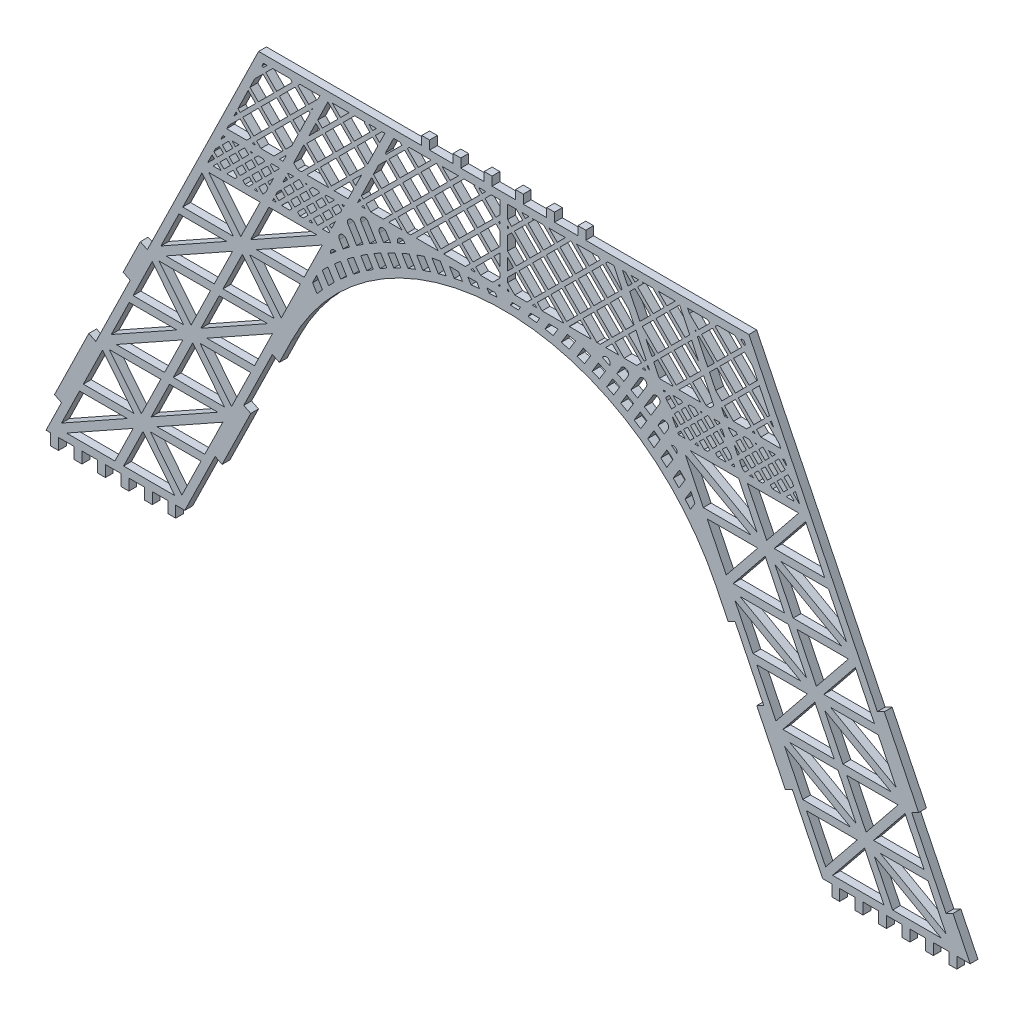
SolidWorks part; units mm, degrees
ref_plane "Front Plane" through (0, 0, 0) normal (0, 0, 1) x (1, 0, 0)
ref_plane "Top Plane" through (0, 0, 0) normal (0, 1, 0) x (1, 0, 0)
ref_plane "Right Plane" through (0, 0, 0) normal (1, 0, 0) x (0, 0, -1)
sketch "Sketch1" plane through (0, 0, 0) normal (0, 0, 1) x (1, 0, 0)
  line L0 (188.1463, 257.1681) -> (189.1366, 258.7906)
  line L1 (189.1366, 258.7906) -> (192.6145, 258.7906)
  line L2 (192.6145, 258.7906) -> (191.391, 256.7861)
  line L3 (216.8981, 258.0721) -> (216.7134, 257.7696)
  line L4 (222.273, 255.3276) -> (223.9481, 258.0721)
  line L5 (226.5088, 256.5092) -> (224.9736, 253.9938)
  line L6 (227.6429, 252.5749) -> (230.9981, 258.0721)
  line L7 (233.5588, 256.5092) -> (230.25, 251.0879)
  line L8 (232.8107, 249.525) -> (236.0655, 254.8577)
  line L9 (238.6262, 253.2948) -> (235.325, 247.8861)
  line L10 (238.0564, 245.9815) -> (239.3624, 248.1213)
  line L11 (241.9232, 246.5583) -> (240.4725, 244.1816)
  line L12 (255.4652, 227.2906) -> (273.7728, 227.2906)
  line L13 (273.7728, 227.2906) -> (248.5492, 241.4217)
  line L14 (248.5492, 241.4217) -> (255.4652, 227.2906)
  line L15 (245.9563, 234.6483) -> (243.9231, 231.317)
  line L16 (246.1067, 229.1363) -> (248.517, 233.0854)
  line L17 (248.517, 233.0854) -> (248.5246, 233.0979)
  line L18 (243.8237, 237.534) -> (241.4409, 233.63)
  line L19 (239.145, 235.6268) -> (241.5153, 239.5103)
  line L20 (238.9003, 241.6056) -> (236.5408, 237.7399)
  line L21 (234.1364, 239.5589) -> (236.4887, 243.4128)
  line L22 (233.7605, 245.3228) -> (231.4135, 241.4775)
  line L23 (228.9029, 243.1225) -> (231.2476, 246.964)
  line L24 (228.6869, 248.5269) -> (226.3422, 244.6854)
  line L25 (223.7314, 246.1663) -> (226.0784, 250.0116)
  line L26 (223.4062, 251.4258) -> (221.0545, 247.5729)
  line L27 (218.3427, 248.8881) -> (220.7013, 252.7525)
  line L28 (217.9315, 254.0068) -> (215.5634, 250.1269)
  line L29 (212.7485, 251.2734) -> (215.1285, 255.1729)
  line L30 (212.2588, 256.2634) -> (209.8641, 252.34)
  line L31 (206.943, 253.3123) -> (209.355, 257.2642)
  line L32 (185.2265, 258.7906) -> (184.4181, 257.4662)
  line L33 (181.3595, 257.5993) -> (182.0866, 258.7906)
  line L34 (182.0866, 258.7906) -> (185.2265, 258.7906)
  line L35 (199.7013, 258.7906) -> (197.8081, 255.6888)
  line L36 (194.6573, 256.2849) -> (196.1866, 258.7906)
  line L37 (196.1866, 258.7906) -> (199.7013, 258.7906)
  line L38 (250.5271, 224.2404) -> (248.4615, 226.6146)
  line L39 (248.4615, 226.6146) -> (250.6784, 230.2468)
  line L40 (250.6784, 230.2468) -> (252.2425, 227.051)
  line L41 (252.2425, 227.051) -> (250.5271, 224.2404)
  line L42 (282.6552, 227.2906) -> (302.1051, 227.2906)
  line L43 (302.1051, 227.2906) -> (294.7576, 242.3034)
  line L44 (294.7576, 242.3034) -> (282.6552, 227.2906)
  line L45 (266.9355, 207.7906) -> (286.6588, 207.7906)
  line L46 (286.6588, 207.7906) -> (279.208, 223.0144)
  line L47 (279.208, 223.0144) -> (266.9355, 207.7906)
  line L48 (301.7424, 188.2906) -> (321.1924, 188.2906)
  line L49 (321.1924, 188.2906) -> (313.8448, 203.3034)
  line L50 (313.8448, 203.3034) -> (301.7424, 188.2906)
  line L51 (311.1903, 204.7906) -> (291.4671, 204.7906)
  line L52 (291.4671, 204.7906) -> (298.9178, 189.5668)
  line L53 (298.9178, 189.5668) -> (311.1903, 204.7906)
  line L54 (295.4706, 185.2906) -> (276.0207, 185.2906)
  line L55 (276.0207, 185.2906) -> (283.3682, 170.2778)
  line L56 (283.3682, 170.2778) -> (295.4706, 185.2906)
  line L57 (286.0228, 168.7906) -> (305.746, 168.7906)
  line L58 (305.746, 168.7906) -> (298.2952, 184.0144)
  line L59 (298.2952, 184.0144) -> (286.0228, 168.7906)
  line L60 (320.8297, 149.2906) -> (340.2796, 149.2906)
  line L61 (340.2796, 149.2906) -> (332.9321, 164.3034)
  line L62 (332.9321, 164.3034) -> (320.8297, 149.2906)
  line L63 (314.5578, 146.2906) -> (295.1079, 146.2906)
  line L64 (295.1079, 146.2906) -> (302.4554, 131.2778)
  line L65 (302.4554, 131.2778) -> (314.5578, 146.2906)
  line L66 (330.2775, 165.7906) -> (310.5543, 165.7906)
  line L67 (310.5543, 165.7906) -> (318.005, 150.5668)
  line L68 (318.005, 150.5668) -> (330.2775, 165.7906)
  line L69 (317.3825, 145.0144) -> (324.8332, 129.7906)
  line L70 (324.8332, 129.7906) -> (305.11, 129.7906)
  line L71 (305.11, 129.7906) -> (317.3825, 145.0144)
  line L72 (264.281, 209.2778) -> (276.3834, 224.2906)
  line L73 (276.3834, 224.2906) -> (256.9335, 224.2906)
  line L74 (256.9335, 224.2906) -> (264.281, 209.2778)
  line L75 (303.5734, 224.2906) -> (285.2658, 224.2906)
  line L76 (285.2658, 224.2906) -> (310.4894, 210.1595)
  line L77 (310.4894, 210.1595) -> (303.5734, 224.2906)
  line L78 (289.9988, 207.7906) -> (308.5797, 207.7906)
  line L79 (308.5797, 207.7906) -> (282.9796, 222.1327)
  line L80 (282.9796, 222.1327) -> (289.9988, 207.7906)
  line L81 (274.5525, 188.2906) -> (292.8601, 188.2906)
  line L82 (292.8601, 188.2906) -> (267.6364, 202.4217)
  line L83 (267.6364, 202.4217) -> (274.5525, 188.2906)
  line L84 (288.127, 204.7906) -> (269.5461, 204.7906)
  line L85 (269.5461, 204.7906) -> (295.1463, 190.4485)
  line L86 (295.1463, 190.4485) -> (288.127, 204.7906)
  line L87 (322.6606, 185.2906) -> (304.353, 185.2906)
  line L88 (304.353, 185.2906) -> (329.5766, 171.1595)
  line L89 (329.5766, 171.1595) -> (322.6606, 185.2906)
  line L90 (309.086, 168.7906) -> (327.667, 168.7906)
  line L91 (327.667, 168.7906) -> (302.0668, 183.1327)
  line L92 (302.0668, 183.1327) -> (309.086, 168.7906)
  line L93 (293.6397, 149.2906) -> (311.9473, 149.2906)
  line L94 (311.9473, 149.2906) -> (286.7237, 163.4217)
  line L95 (286.7237, 163.4217) -> (293.6397, 149.2906)
  line L96 (307.2143, 165.7906) -> (288.6333, 165.7906)
  line L97 (288.6333, 165.7906) -> (314.2335, 151.4485)
  line L98 (314.2335, 151.4485) -> (307.2143, 165.7906)
  line L99 (321.154, 144.1327) -> (328.1733, 129.7906)
  line L100 (328.1733, 129.7906) -> (346.7542, 129.7906)
  line L101 (346.7542, 129.7906) -> (321.154, 144.1327)
  line L102 (323.4402, 146.2906) -> (341.7478, 146.2906)
  line L103 (341.7478, 146.2906) -> (348.6638, 132.1595)
  line L104 (348.6638, 132.1595) -> (323.4402, 146.2906)
  line L105 (206.3818, 258.1852) -> (203.9493, 254.1999)
  line L106 (200.9169, 254.9899) -> (203.2366, 258.7906)
  line L107 (203.2366, 258.7906) -> (206.3818, 258.1852)
  line L108 (285.8115, 258.7906) -> (286.6885, 258.7906)
  line L109 (286.6885, 258.7906) -> (287.5292, 257.073)
  line L110 (287.5292, 257.073) -> (285.8115, 258.7906)
  line L111 (241.003, 258.7906) -> (240.3622, 258.1498)
  line L112 (240.3622, 258.1498) -> (240.0486, 258.7906)
  line L113 (240.0486, 258.7906) -> (241.003, 258.7906)
  line L114 (247.4833, 258.2475) -> (246.9402, 258.7906)
  line L115 (246.9402, 258.7906) -> (243.8115, 258.7906)
  line L116 (243.8115, 258.7906) -> (245.919, 256.6832)
  line L117 (245.919, 256.6832) -> (247.4833, 258.2475)
  line L118 (244.8583, 255.6225) -> (242.4073, 258.0735)
  line L119 (242.4073, 258.0735) -> (241.0593, 256.7256)
  line L120 (241.0593, 256.7256) -> (241.4741, 255.8781)
  line L121 (241.4741, 255.8781) -> (243.294, 254.0582)
  line L122 (243.294, 254.0582) -> (244.8583, 255.6225)
  line L123 (245.9216, 246.7906) -> (248.4402, 246.7906)
  line L124 (248.4402, 246.7906) -> (246.8057, 248.4251)
  line L125 (246.8057, 248.4251) -> (245.675, 247.2945)
  line L126 (245.675, 247.2945) -> (245.9216, 246.7906)
  line L127 (255.0498, 258.7906) -> (254.3115, 258.7906)
  line L128 (254.3115, 258.7906) -> (254.6807, 258.4215)
  line L129 (254.6807, 258.4215) -> (255.0498, 258.7906)
  line L130 (253.62, 257.3608) -> (252.1902, 258.7906)
  line L131 (252.1902, 258.7906) -> (250.1477, 258.7906)
  line L132 (250.1477, 258.7906) -> (249.6046, 258.2475)
  line L133 (249.6046, 258.2475) -> (252.0557, 255.7965)
  line L134 (252.0557, 255.7965) -> (253.62, 257.3608)
  line L135 (250.995, 254.7358) -> (248.544, 257.1868)
  line L136 (248.544, 257.1868) -> (246.9796, 255.6225)
  line L137 (246.9796, 255.6225) -> (249.4307, 253.1715)
  line L138 (249.4307, 253.1715) -> (250.995, 254.7358)
  line L139 (248.37, 252.1108) -> (245.919, 254.5618)
  line L140 (245.919, 254.5618) -> (244.3546, 252.9975)
  line L141 (244.3546, 252.9975) -> (246.8057, 250.5465)
  line L142 (246.8057, 250.5465) -> (248.37, 252.1108)
  line L143 (245.745, 249.4858) -> (243.5074, 251.7234)
  line L144 (243.5074, 251.7234) -> (244.978, 248.7187)
  line L145 (244.978, 248.7187) -> (245.745, 249.4858)
  line L146 (252.1945, 246.7906) -> (253.6902, 246.7906)
  line L147 (253.6902, 246.7906) -> (252.9424, 247.5384)
  line L148 (252.9424, 247.5384) -> (252.1945, 246.7906)
  line L149 (261.878, 256.4741) -> (263.747, 254.6051)
  line L150 (263.747, 254.6051) -> (262.5187, 257.1148)
  line L151 (262.5187, 257.1148) -> (261.878, 256.4741)
  line L152 (261.8217, 258.5391) -> (261.6986, 258.7906)
  line L153 (261.6986, 258.7906) -> (259.5615, 258.7906)
  line L154 (259.5615, 258.7906) -> (260.8174, 257.5348)
  line L155 (260.8174, 257.5348) -> (261.8217, 258.5391)
  line L156 (259.7567, 256.4741) -> (257.4402, 258.7906)
  line L157 (257.4402, 258.7906) -> (257.1711, 258.7906)
  line L158 (257.1711, 258.7906) -> (255.7413, 257.3608)
  line L159 (255.7413, 257.3608) -> (258.1924, 254.9098)
  line L160 (258.1924, 254.9098) -> (259.7567, 256.4741)
  line L161 (257.1317, 253.8491) -> (254.6807, 256.3001)
  line L162 (254.6807, 256.3001) -> (253.1163, 254.7358)
  line L163 (253.1163, 254.7358) -> (255.5674, 252.2848)
  line L164 (255.5674, 252.2848) -> (257.1317, 253.8491)
  line L165 (254.5067, 251.2241) -> (252.0557, 253.6751)
  line L166 (252.0557, 253.6751) -> (250.4913, 252.1108)
  line L167 (250.4913, 252.1108) -> (252.9424, 249.6598)
  line L168 (252.9424, 249.6598) -> (254.5067, 251.2241)
  line L169 (251.8817, 248.5991) -> (249.4307, 251.0501)
  line L170 (249.4307, 251.0501) -> (247.8663, 249.4858)
  line L171 (247.8663, 249.4858) -> (250.3174, 247.0348)
  line L172 (250.3174, 247.0348) -> (251.8817, 248.5991)
  line L173 (268.5184, 258.2124) -> (267.9402, 258.7906)
  line L174 (267.9402, 258.7906) -> (265.0386, 258.7906)
  line L175 (265.0386, 258.7906) -> (265.2562, 258.3459)
  line L176 (265.2562, 258.3459) -> (266.9541, 256.6481)
  line L177 (266.9541, 256.6481) -> (268.5184, 258.2124)
  line L178 (263.2684, 252.9624) -> (260.8174, 255.4134)
  line L179 (260.8174, 255.4134) -> (259.253, 253.8491)
  line L180 (259.253, 253.8491) -> (261.7041, 251.3981)
  line L181 (261.7041, 251.3981) -> (263.2684, 252.9624)
  line L182 (260.6434, 250.3374) -> (258.1924, 252.7884)
  line L183 (258.1924, 252.7884) -> (256.628, 251.2241)
  line L184 (256.628, 251.2241) -> (259.0791, 248.7731)
  line L185 (259.0791, 248.7731) -> (260.6434, 250.3374)
  line L186 (258.0184, 247.7124) -> (255.5674, 250.1634)
  line L187 (255.5674, 250.1634) -> (254.003, 248.5991)
  line L188 (254.003, 248.5991) -> (255.8115, 246.7906)
  line L189 (255.8115, 246.7906) -> (257.0966, 246.7906)
  line L190 (257.0966, 246.7906) -> (258.0184, 247.7124)
  line L191 (266.2764, 246.8257) -> (266.3115, 246.7906)
  line L192 (266.3115, 246.7906) -> (267.5716, 246.7906)
  line L193 (267.5716, 246.7906) -> (267.1344, 247.6837)
  line L194 (267.1344, 247.6837) -> (266.2764, 246.8257)
  line L195 (276.12, 258.7906) -> (275.3115, 258.7906)
  line L196 (275.3115, 258.7906) -> (275.7158, 258.3864)
  line L197 (275.7158, 258.3864) -> (276.12, 258.7906)
  line L198 (274.6551, 257.3257) -> (273.1902, 258.7906)
  line L199 (273.1902, 258.7906) -> (271.2179, 258.7906)
  line L200 (271.2179, 258.7906) -> (270.6397, 258.2124)
  line L201 (270.6397, 258.2124) -> (273.0908, 255.7614)
  line L202 (273.0908, 255.7614) -> (274.6551, 257.3257)
  line L203 (272.0301, 254.7007) -> (269.5791, 257.1517)
  line L204 (269.5791, 257.1517) -> (268.0147, 255.5874)
  line L205 (268.0147, 255.5874) -> (270.4658, 253.1364)
  line L206 (270.4658, 253.1364) -> (272.0301, 254.7007)
  line L207 (269.4051, 252.0757) -> (267.2896, 254.1912)
  line L208 (267.2896, 254.1912) -> (268.6799, 251.3505)
  line L209 (268.6799, 251.3505) -> (269.4051, 252.0757)
  line L210 (266.4374, 249.108) -> (265.7804, 250.4504)
  line L211 (265.7804, 250.4504) -> (264.3291, 251.9017)
  line L212 (264.3291, 251.9017) -> (262.7647, 250.3374)
  line L213 (262.7647, 250.3374) -> (265.2158, 247.8864)
  line L214 (265.2158, 247.8864) -> (266.4374, 249.108)
  line L215 (264.1551, 246.8257) -> (261.7041, 249.2767)
  line L216 (261.7041, 249.2767) -> (260.1397, 247.7124)
  line L217 (260.1397, 247.7124) -> (261.0615, 246.7906)
  line L218 (261.0615, 246.7906) -> (264.12, 246.7906)
  line L219 (264.12, 246.7906) -> (264.1551, 246.8257)
  line L220 (276.0591, 229.4485) -> (269.0398, 243.7906)
  line L221 (269.0398, 243.7906) -> (250.4589, 243.7906)
  line L222 (250.4589, 243.7906) -> (276.0591, 229.4485)
  line L223 (273.2647, 246.7906) -> (274.6902, 246.7906)
  line L224 (274.6902, 246.7906) -> (273.9775, 247.5033)
  line L225 (273.9775, 247.5033) -> (273.2647, 246.7906)
  line L226 (283.1434, 258.7906) -> (280.5615, 258.7906)
  line L227 (280.5615, 258.7906) -> (281.8525, 257.4997)
  line L228 (281.8525, 257.4997) -> (283.1434, 258.7906)
  line L229 (280.7918, 256.439) -> (278.4402, 258.7906)
  line L230 (278.4402, 258.7906) -> (278.2413, 258.7906)
  line L231 (278.2413, 258.7906) -> (276.7764, 257.3257)
  line L232 (276.7764, 257.3257) -> (279.2275, 254.8747)
  line L233 (279.2275, 254.8747) -> (280.7918, 256.439)
  line L234 (278.1668, 253.814) -> (275.7158, 256.265)
  line L235 (275.7158, 256.265) -> (274.1514, 254.7007)
  line L236 (274.1514, 254.7007) -> (276.6025, 252.2497)
  line L237 (276.6025, 252.2497) -> (278.1668, 253.814)
  line L238 (275.5418, 251.189) -> (273.0908, 253.64)
  line L239 (273.0908, 253.64) -> (271.5264, 252.0757)
  line L240 (271.5264, 252.0757) -> (273.9775, 249.6247)
  line L241 (273.9775, 249.6247) -> (275.5418, 251.189)
  line L242 (272.9168, 248.564) -> (270.4658, 251.015)
  line L243 (270.4658, 251.015) -> (269.377, 249.9262)
  line L244 (269.377, 249.9262) -> (270.2886, 248.0636)
  line L245 (270.2886, 248.0636) -> (271.3525, 246.9997)
  line L246 (271.3525, 246.9997) -> (272.9168, 248.564)
  line L247 (286.9285, 255.5523) -> (284.4775, 258.0033)
  line L248 (284.4775, 258.0033) -> (282.9131, 256.439)
  line L249 (282.9131, 256.439) -> (285.3642, 253.988)
  line L250 (285.3642, 253.988) -> (286.9285, 255.5523)
  line L251 (284.3035, 252.9273) -> (281.8525, 255.3783)
  line L252 (281.8525, 255.3783) -> (280.2881, 253.814)
  line L253 (280.2881, 253.814) -> (282.7392, 251.363)
  line L254 (282.7392, 251.363) -> (284.3035, 252.9273)
  line L255 (281.6785, 250.3023) -> (279.2275, 252.7533)
  line L256 (279.2275, 252.7533) -> (277.6631, 251.189)
  line L257 (277.6631, 251.189) -> (280.1142, 248.738)
  line L258 (280.1142, 248.738) -> (281.6785, 250.3023)
  line L259 (279.0535, 247.6773) -> (276.6025, 250.1283)
  line L260 (276.6025, 250.1283) -> (275.0381, 248.564)
  line L261 (275.0381, 248.564) -> (276.8115, 246.7906)
  line L262 (276.8115, 246.7906) -> (278.1668, 246.7906)
  line L263 (278.1668, 246.7906) -> (279.0535, 247.6773)
  line L264 (279.8306, 228.5668) -> (292.1031, 243.7906)
  line L265 (292.1031, 243.7906) -> (272.3798, 243.7906)
  line L266 (272.3798, 243.7906) -> (279.8306, 228.5668)
  line L267 (287.3115, 246.7906) -> (290.4402, 246.7906)
  line L268 (290.4402, 246.7906) -> (288.8759, 248.355)
  line L269 (288.8759, 248.355) -> (287.3115, 246.7906)
  line L270 (289.9365, 249.4156) -> (292.5615, 246.7906)
  line L271 (292.5615, 246.7906) -> (290.8364, 250.3155)
  line L272 (290.8364, 250.3155) -> (289.9365, 249.4156)
  line L273 (288.8759, 250.4763) -> (286.4248, 252.9273)
  line L274 (286.4248, 252.9273) -> (287.9892, 254.4917)
  line L275 (287.9892, 254.4917) -> (289.5625, 252.9183)
  line L276 (289.5625, 252.9183) -> (290.1393, 251.7397)
  line L277 (290.1393, 251.7397) -> (288.8759, 250.4763)
  line L278 (287.8152, 249.4156) -> (285.3642, 251.8667)
  line L279 (285.3642, 251.8667) -> (283.7998, 250.3023)
  line L280 (283.7998, 250.3023) -> (286.2509, 247.8513)
  line L281 (286.2509, 247.8513) -> (287.8152, 249.4156)
  line L282 (282.7392, 249.2417) -> (281.1748, 247.6773)
  line L283 (281.1748, 247.6773) -> (282.0615, 246.7906)
  line L284 (282.0615, 246.7906) -> (285.1902, 246.7906)
  line L285 (285.1902, 246.7906) -> (282.7392, 249.2417)
  line L286 (204.0615, 261.7906) -> (212.4402, 261.7906)
  line L287 (212.4402, 261.7906) -> (208.1885, 266.0423)
  line L288 (208.1885, 266.0423) -> (203.9992, 261.8529)
  line L289 (203.9992, 261.8529) -> (204.0615, 261.7906)
  line L290 (228.1279, 288.1029) -> (226.4996, 286.4747)
  line L291 (226.4996, 286.4747) -> (224.464, 290.6338)
  line L292 (224.464, 290.6338) -> (225.597, 290.6338)
  line L293 (225.597, 290.6338) -> (228.1279, 288.1029)
  line L294 (227.7183, 290.6338) -> (229.1885, 289.1636)
  line L295 (229.1885, 289.1636) -> (230.6588, 290.6338)
  line L296 (230.6588, 290.6338) -> (227.7183, 290.6338)
  line L297 (217.9836, 261.7906) -> (222.9402, 261.7906)
  line L298 (222.9402, 261.7906) -> (220.4619, 264.2689)
  line L299 (220.4619, 264.2689) -> (217.9836, 261.7906)
  line L300 (213.4385, 271.2923) -> (209.2492, 267.1029)
  line L301 (209.2492, 267.1029) -> (214.5615, 261.7906)
  line L302 (214.5615, 261.7906) -> (215.8623, 261.7906)
  line L303 (215.8623, 261.7906) -> (219.4013, 265.3296)
  line L304 (219.4013, 265.3296) -> (213.4385, 271.2923)
  line L305 (218.6885, 276.5423) -> (214.4992, 272.3529)
  line L306 (214.4992, 272.3529) -> (220.4619, 266.3902)
  line L307 (220.4619, 266.3902) -> (224.6513, 270.5796)
  line L308 (224.6513, 270.5796) -> (218.6885, 276.5423)
  line L309 (226.9012, 278.8296) -> (223.9385, 281.7923)
  line L310 (223.9385, 281.7923) -> (219.7492, 277.6029)
  line L311 (219.7492, 277.6029) -> (225.7119, 271.6402)
  line L312 (225.7119, 271.6402) -> (228.8728, 274.8011)
  line L313 (228.8728, 274.8011) -> (226.9012, 278.8296)
  line L314 (232.0304, 261.7906) -> (233.4402, 261.7906)
  line L315 (233.4402, 261.7906) -> (232.7353, 262.4955)
  line L316 (232.7353, 262.4955) -> (232.0304, 261.7906)
  line L317 (238.5804, 261.7906) -> (243.9402, 261.7906)
  line L318 (243.9402, 261.7906) -> (237.9853, 267.7455)
  line L319 (237.9853, 267.7455) -> (236.4281, 266.1883)
  line L320 (236.4281, 266.1883) -> (238.5804, 261.7906)
  line L321 (234.9325, 262.4196) -> (234.1856, 263.9458)
  line L322 (234.1856, 263.9458) -> (233.796, 263.5562)
  line L323 (233.796, 263.5562) -> (234.9325, 262.4196)
  line L324 (225.7119, 269.5189) -> (221.5226, 265.3296)
  line L325 (221.5226, 265.3296) -> (225.0615, 261.7906)
  line L326 (225.0615, 261.7906) -> (229.9091, 261.7906)
  line L327 (229.9091, 261.7906) -> (231.6747, 263.5562)
  line L328 (231.6747, 263.5562) -> (225.7119, 269.5189)
  line L329 (229.5699, 273.3768) -> (226.7726, 270.5796)
  line L330 (226.7726, 270.5796) -> (232.7353, 264.6168)
  line L331 (232.7353, 264.6168) -> (233.4885, 265.37)
  line L332 (233.4885, 265.37) -> (229.5699, 273.3768)
  line L333 (236.9247, 268.8062) -> (235.731, 267.6125)
  line L334 (235.731, 267.6125) -> (233.4428, 272.2881)
  line L335 (233.4428, 272.2881) -> (236.9247, 268.8062)
  line L336 (187.0948, 289.2574) -> (185.7183, 290.6338)
  line L337 (185.7183, 290.6338) -> (188.4713, 290.6338)
  line L338 (188.4713, 290.6338) -> (187.0948, 289.2574)
  line L339 (189.8429, 261.7906) -> (191.4402, 261.7906)
  line L340 (191.4402, 261.7906) -> (190.6416, 262.5892)
  line L341 (190.6416, 262.5892) -> (189.8429, 261.7906)
  line L342 (193.5615, 261.7906) -> (201.8155, 261.7906)
  line L343 (201.8155, 261.7906) -> (201.8779, 261.8529)
  line L344 (201.8779, 261.8529) -> (195.8916, 267.8392)
  line L345 (195.8916, 267.8392) -> (191.7022, 263.6499)
  line L346 (191.7022, 263.6499) -> (193.5615, 261.7906)
  line L347 (188.8682, 274.8626) -> (184.6788, 270.6733)
  line L348 (184.6788, 270.6733) -> (190.6416, 264.7106)
  line L349 (190.6416, 264.7106) -> (194.8309, 268.8999)
  line L350 (194.8309, 268.8999) -> (188.8682, 274.8626)
  line L351 (250.2823, 265.9485) -> (254.4402, 261.7906)
  line L352 (254.4402, 261.7906) -> (246.1244, 261.7906)
  line L353 (246.1244, 261.7906) -> (250.2823, 265.9485)
  line L354 (255.7157, 271.0151) -> (255.5323, 271.1985)
  line L355 (255.5323, 271.1985) -> (251.3429, 267.0092)
  line L356 (251.3429, 267.0092) -> (256.5615, 261.7906)
  line L357 (256.5615, 261.7906) -> (258.0498, 261.7906)
  line L358 (258.0498, 261.7906) -> (259.5138, 263.2546)
  line L359 (259.5138, 263.2546) -> (255.7157, 271.0151)
  line L360 (272.3429, 288.0092) -> (272.4321, 287.92)
  line L361 (272.4321, 287.92) -> (272.3735, 288.0398)
  line L362 (272.3735, 288.0398) -> (272.3429, 288.0092)
  line L363 (271.2823, 289.0699) -> (269.7183, 290.6338)
  line L364 (269.7183, 290.6338) -> (271.1039, 290.6338)
  line L365 (271.1039, 290.6338) -> (271.6765, 289.464)
  line L366 (271.6765, 289.464) -> (271.2823, 289.0699)
  line L367 (260.2109, 261.8303) -> (260.2303, 261.7906)
  line L368 (260.2303, 261.7906) -> (260.1711, 261.7906)
  line L369 (260.1711, 261.7906) -> (260.2109, 261.8303)
  line L370 (262.4534, 264.0728) -> (263.5703, 261.7906)
  line L371 (263.5703, 261.7906) -> (264.9402, 261.7906)
  line L372 (264.9402, 261.7906) -> (262.5557, 264.1751)
  line L373 (262.5557, 264.1751) -> (262.4534, 264.0728)
  line L374 (273.0557, 276.7965) -> (267.0929, 282.7592)
  line L375 (267.0929, 282.7592) -> (271.2823, 286.9485)
  line L376 (271.2823, 286.9485) -> (274.4655, 283.7653)
  line L377 (274.4655, 283.7653) -> (276.2922, 280.033)
  line L378 (276.2922, 280.033) -> (273.0557, 276.7965)
  line L379 (271.995, 275.7358) -> (266.0323, 281.6985)
  line L380 (266.0323, 281.6985) -> (261.8429, 277.5092)
  line L381 (261.8429, 277.5092) -> (267.8057, 271.5465)
  line L382 (267.8057, 271.5465) -> (271.995, 275.7358)
  line L383 (266.745, 270.4858) -> (260.7823, 276.4485)
  line L384 (260.7823, 276.4485) -> (257.8377, 273.5039)
  line L385 (257.8377, 273.5039) -> (260.2239, 268.6282)
  line L386 (260.2239, 268.6282) -> (262.5557, 266.2965)
  line L387 (262.5557, 266.2965) -> (266.745, 270.4858)
  line L388 (260.046, 289.8062) -> (266.0323, 283.8199)
  line L389 (266.0323, 283.8199) -> (270.2216, 288.0092)
  line L390 (270.2216, 288.0092) -> (267.597, 290.6338)
  line L391 (267.597, 290.6338) -> (260.8737, 290.6338)
  line L392 (260.8737, 290.6338) -> (260.046, 289.8062)
  line L393 (239.046, 268.8062) -> (245.0323, 262.8199)
  line L394 (245.0323, 262.8199) -> (249.2216, 267.0092)
  line L395 (249.2216, 267.0092) -> (243.2353, 272.9955)
  line L396 (243.2353, 272.9955) -> (239.046, 268.8062)
  line L397 (244.296, 274.0562) -> (250.2823, 268.0699)
  line L398 (250.2823, 268.0699) -> (254.4716, 272.2592)
  line L399 (254.4716, 272.2592) -> (248.4853, 278.2455)
  line L400 (248.4853, 278.2455) -> (244.296, 274.0562)
  line L401 (249.546, 279.3062) -> (253.6823, 275.1698)
  line L402 (253.6823, 275.1698) -> (250.9639, 280.7241)
  line L403 (250.9639, 280.7241) -> (249.546, 279.3062)
  line L404 (253.2065, 282.9666) -> (257.1406, 274.9282)
  line L405 (257.1406, 274.9282) -> (259.7216, 277.5092)
  line L406 (259.7216, 277.5092) -> (253.7353, 283.4955)
  line L407 (253.7353, 283.4955) -> (253.2065, 282.9666)
  line L408 (254.796, 284.5562) -> (260.7823, 278.5699)
  line L409 (260.7823, 278.5699) -> (264.9716, 282.7592)
  line L410 (264.9716, 282.7592) -> (258.9853, 288.7455)
  line L411 (258.9853, 288.7455) -> (254.796, 284.5562)
  line L412 (257.9247, 289.8062) -> (257.097, 290.6338)
  line L413 (257.097, 290.6338) -> (249.454, 290.6338)
  line L414 (249.454, 290.6338) -> (250.1592, 289.1929)
  line L415 (250.1592, 289.1929) -> (253.7353, 285.6168)
  line L416 (253.7353, 285.6168) -> (257.9247, 289.8062)
  line L417 (252.6747, 284.5562) -> (252.1926, 285.0382)
  line L418 (252.1926, 285.0382) -> (252.5094, 284.3909)
  line L419 (252.5094, 284.3909) -> (252.6747, 284.5562)
  line L420 (232.0226, 275.8296) -> (237.9853, 269.8668)
  line L421 (237.9853, 269.8668) -> (242.1747, 274.0562)
  line L422 (242.1747, 274.0562) -> (236.2119, 280.0189)
  line L423 (236.2119, 280.0189) -> (232.0226, 275.8296)
  line L424 (229.1885, 287.0423) -> (227.1967, 285.0504)
  line L425 (227.1967, 285.0504) -> (231.1153, 277.0436)
  line L426 (231.1153, 277.0436) -> (235.1513, 281.0796)
  line L427 (235.1513, 281.0796) -> (229.1885, 287.0423)
  line L428 (240.4013, 286.3296) -> (236.2119, 282.1402)
  line L429 (236.2119, 282.1402) -> (230.2492, 288.1029)
  line L430 (230.2492, 288.1029) -> (232.4285, 290.2823)
  line L431 (232.4285, 290.2823) -> (232.077, 290.6338)
  line L432 (232.077, 290.6338) -> (236.097, 290.6338)
  line L433 (236.097, 290.6338) -> (240.4013, 286.3296)
  line L434 (241.4619, 287.3902) -> (238.2183, 290.6338)
  line L435 (238.2183, 290.6338) -> (244.7056, 290.6338)
  line L436 (244.7056, 290.6338) -> (241.4619, 287.3902)
  line L437 (242.5226, 286.3296) -> (248.4853, 280.3668)
  line L438 (248.4853, 280.3668) -> (250.2669, 282.1484)
  line L439 (250.2669, 282.1484) -> (246.3482, 290.1552)
  line L440 (246.3482, 290.1552) -> (242.5226, 286.3296)
  line L441 (237.2726, 281.0796) -> (243.2353, 275.1168)
  line L442 (243.2353, 275.1168) -> (247.4247, 279.3062)
  line L443 (247.4247, 279.3062) -> (241.4619, 285.2689)
  line L444 (241.4619, 285.2689) -> (237.2726, 281.0796)
  line L445 (217.9522, 289.8999) -> (223.9385, 283.9136)
  line L446 (223.9385, 283.9136) -> (224.2571, 284.2322)
  line L447 (224.2571, 284.2322) -> (221.124, 290.6338)
  line L448 (221.124, 290.6338) -> (218.6862, 290.6338)
  line L449 (218.6862, 290.6338) -> (217.9522, 289.8999)
  line L450 (196.9522, 268.8999) -> (202.9385, 262.9136)
  line L451 (202.9385, 262.9136) -> (207.1279, 267.1029)
  line L452 (207.1279, 267.1029) -> (201.1416, 273.0892)
  line L453 (201.1416, 273.0892) -> (196.9522, 268.8999)
  line L454 (202.2022, 274.1499) -> (208.1885, 268.1636)
  line L455 (208.1885, 268.1636) -> (212.3779, 272.3529)
  line L456 (212.3779, 272.3529) -> (206.3916, 278.3392)
  line L457 (206.3916, 278.3392) -> (202.2022, 274.1499)
  line L458 (207.4522, 279.3999) -> (213.4385, 273.4136)
  line L459 (213.4385, 273.4136) -> (217.6279, 277.6029)
  line L460 (217.6279, 277.6029) -> (211.6416, 283.5892)
  line L461 (211.6416, 283.5892) -> (207.4522, 279.3999)
  line L462 (212.7022, 284.6499) -> (218.6885, 278.6636)
  line L463 (218.6885, 278.6636) -> (222.8779, 282.8529)
  line L464 (222.8779, 282.8529) -> (216.8916, 288.8392)
  line L465 (216.8916, 288.8392) -> (212.7022, 284.6499)
  line L466 (215.8309, 289.8999) -> (215.097, 290.6338)
  line L467 (215.097, 290.6338) -> (206.7183, 290.6338)
  line L468 (206.7183, 290.6338) -> (211.6416, 285.7106)
  line L469 (211.6416, 285.7106) -> (215.8309, 289.8999)
  line L470 (189.9288, 275.9233) -> (195.8916, 269.9606)
  line L471 (195.8916, 269.9606) -> (200.0809, 274.1499)
  line L472 (200.0809, 274.1499) -> (194.1182, 280.1126)
  line L473 (194.1182, 280.1126) -> (189.9288, 275.9233)
  line L474 (187.0948, 287.136) -> (182.9054, 282.9467)
  line L475 (182.9054, 282.9467) -> (188.8682, 276.984)
  line L476 (188.8682, 276.984) -> (193.0575, 281.1733)
  line L477 (193.0575, 281.1733) -> (187.0948, 287.136)
  line L478 (198.3075, 286.4233) -> (194.1182, 282.234)
  line L479 (194.1182, 282.234) -> (188.1554, 288.1967)
  line L480 (188.1554, 288.1967) -> (190.241, 290.2823)
  line L481 (190.241, 290.2823) -> (189.8895, 290.6338)
  line L482 (189.8895, 290.6338) -> (194.097, 290.6338)
  line L483 (194.097, 290.6338) -> (198.3075, 286.4233)
  line L484 (195.1788, 281.1733) -> (201.1416, 275.2106)
  line L485 (201.1416, 275.2106) -> (205.3309, 279.3999)
  line L486 (205.3309, 279.3999) -> (199.3682, 285.3626)
  line L487 (199.3682, 285.3626) -> (195.1788, 281.1733)
  line L488 (199.3682, 287.484) -> (196.2183, 290.6338)
  line L489 (196.2183, 290.6338) -> (202.5181, 290.6338)
  line L490 (202.5181, 290.6338) -> (199.3682, 287.484)
  line L491 (200.4288, 286.4233) -> (206.3916, 280.4606)
  line L492 (206.3916, 280.4606) -> (210.5809, 284.6499)
  line L493 (210.5809, 284.6499) -> (204.6182, 290.6126)
  line L494 (204.6182, 290.6126) -> (200.4288, 286.4233)
  line L495 (267.8057, 269.4251) -> (263.6163, 265.2358)
  line L496 (263.6163, 265.2358) -> (267.0615, 261.7906)
  line L497 (267.0615, 261.7906) -> (272.0966, 261.7906)
  line L498 (272.0966, 261.7906) -> (273.7684, 263.4624)
  line L499 (273.7684, 263.4624) -> (267.8057, 269.4251)
  line L500 (281.1397, 268.7124) -> (282.4968, 267.3553)
  line L501 (282.4968, 267.3553) -> (281.605, 269.1776)
  line L502 (281.605, 269.1776) -> (281.1397, 268.7124)
  line L503 (275.8897, 263.4624) -> (277.5615, 261.7906)
  line L504 (277.5615, 261.7906) -> (285.2203, 261.7906)
  line L505 (285.2203, 261.7906) -> (284.5302, 263.2006)
  line L506 (284.5302, 263.2006) -> (280.0791, 267.6517)
  line L507 (280.0791, 267.6517) -> (275.8897, 263.4624)
  line L508 (274.8291, 262.4017) -> (275.4402, 261.7906)
  line L509 (275.4402, 261.7906) -> (274.2179, 261.7906)
  line L510 (274.2179, 261.7906) -> (274.8291, 262.4017)
  line L511 (279.0184, 268.7124) -> (273.0557, 274.6751)
  line L512 (273.0557, 274.6751) -> (268.8663, 270.4858)
  line L513 (268.8663, 270.4858) -> (274.8291, 264.5231)
  line L514 (274.8291, 264.5231) -> (279.0184, 268.7124)
  line L515 (280.0791, 269.7731) -> (274.1163, 275.7358)
  line L516 (274.1163, 275.7358) -> (276.9892, 278.6087)
  line L517 (276.9892, 278.6087) -> (280.9079, 270.6019)
  line L518 (280.9079, 270.6019) -> (280.0791, 269.7731)
  line L519 (165.017, 258.7906) -> (168.4948, 258.7906)
  line L520 (168.4948, 258.7906) -> (169.4851, 257.1681)
  line L521 (166.2404, 256.7861) -> (165.017, 258.7906)
  line L522 (140.918, 257.7696) -> (140.7334, 258.0721)
  line L523 (135.3585, 255.3276) -> (133.6834, 258.0721)
  line L524 (131.1227, 256.5092) -> (132.6579, 253.9938)
  line L525 (129.9886, 252.5749) -> (126.6334, 258.0721)
  line L526 (124.0727, 256.5092) -> (127.3815, 251.0879)
  line L527 (124.8208, 249.525) -> (121.566, 254.8577)
  line L528 (119.0053, 253.2948) -> (122.3064, 247.8861)
  line L529 (119.575, 245.9815) -> (118.269, 248.1213)
  line L530 (115.7083, 246.5583) -> (117.159, 244.1816)
  line L531 (102.1662, 227.2906) -> (83.8586, 227.2906)
  line L532 (83.8586, 227.2906) -> (109.0822, 241.4217)
  line L533 (109.0822, 241.4217) -> (102.1662, 227.2906)
  line L534 (109.1069, 233.0979) -> (109.1144, 233.0854)
  line L535 (109.1144, 233.0854) -> (111.5247, 229.1363)
  line L536 (113.7084, 231.317) -> (111.6751, 234.6483)
  line L537 (113.8077, 237.534) -> (116.1905, 233.63)
  line L538 (118.4865, 235.6268) -> (116.1162, 239.5103)
  line L539 (118.7312, 241.6056) -> (121.0906, 237.7399)
  line L540 (123.495, 239.5589) -> (121.1428, 243.4128)
  line L541 (123.8709, 245.3228) -> (126.2179, 241.4775)
  line L542 (128.7286, 243.1225) -> (126.3839, 246.964)
  line L543 (128.9446, 248.5269) -> (131.2893, 244.6854)
  line L544 (133.9001, 246.1663) -> (131.5531, 250.0116)
  line L545 (134.2253, 251.4258) -> (136.5769, 247.5729)
  line L546 (139.2888, 248.8881) -> (136.9302, 252.7525)
  line L547 (139.7, 254.0068) -> (142.0681, 250.1269)
  line L548 (144.8829, 251.2734) -> (142.5029, 255.1729)
  line L549 (145.3727, 256.2634) -> (147.7673, 252.34)
  line L550 (150.6885, 253.3123) -> (148.2765, 257.2642)
  line L551 (172.405, 258.7906) -> (173.2133, 257.4662)
  line L552 (176.2719, 257.5993) -> (175.5448, 258.7906)
  line L553 (175.5448, 258.7906) -> (172.405, 258.7906)
  line L554 (157.9302, 258.7906) -> (159.8234, 255.6888)
  line L555 (162.9742, 256.2849) -> (161.4448, 258.7906)
  line L556 (161.4448, 258.7906) -> (157.9302, 258.7906)
  line L557 (107.1044, 224.2404) -> (109.1699, 226.6146)
  line L558 (109.1699, 226.6146) -> (106.9531, 230.2468)
  line L559 (106.9531, 230.2468) -> (105.389, 227.051)
  line L560 (105.389, 227.051) -> (107.1044, 224.2404)
  line L561 (62.8739, 242.3034) -> (55.5263, 227.2906)
  line L562 (55.5263, 227.2906) -> (74.9763, 227.2906)
  line L563 (74.9763, 227.2906) -> (62.8739, 242.3034)
  line L564 (90.6959, 207.7906) -> (70.9727, 207.7906)
  line L565 (70.9727, 207.7906) -> (78.4235, 223.0144)
  line L566 (78.4235, 223.0144) -> (90.6959, 207.7906)
  line L567 (43.7866, 203.3034) -> (36.4391, 188.2906)
  line L568 (36.4391, 188.2906) -> (55.889, 188.2906)
  line L569 (55.889, 188.2906) -> (43.7866, 203.3034)
  line L570 (46.4412, 204.7906) -> (66.1644, 204.7906)
  line L571 (66.1644, 204.7906) -> (58.7136, 189.5668)
  line L572 (58.7136, 189.5668) -> (46.4412, 204.7906)
  line L573 (74.2632, 170.2778) -> (81.6108, 185.2906)
  line L574 (81.6108, 185.2906) -> (62.1608, 185.2906)
  line L575 (62.1608, 185.2906) -> (74.2632, 170.2778)
  line L576 (71.6087, 168.7906) -> (51.8855, 168.7906)
  line L577 (51.8855, 168.7906) -> (59.3362, 184.0144)
  line L578 (59.3362, 184.0144) -> (71.6087, 168.7906)
  line L579 (24.6994, 164.3034) -> (17.3519, 149.2906)
  line L580 (17.3519, 149.2906) -> (36.8018, 149.2906)
  line L581 (36.8018, 149.2906) -> (24.6994, 164.3034)
  line L582 (55.176, 131.2778) -> (62.5235, 146.2906)
  line L583 (62.5235, 146.2906) -> (43.0736, 146.2906)
  line L584 (43.0736, 146.2906) -> (55.176, 131.2778)
  line L585 (27.354, 165.7906) -> (47.0772, 165.7906)
  line L586 (47.0772, 165.7906) -> (39.6264, 150.5668)
  line L587 (39.6264, 150.5668) -> (27.354, 165.7906)
  line L588 (52.5215, 129.7906) -> (32.7982, 129.7906)
  line L589 (32.7982, 129.7906) -> (40.249, 145.0144)
  line L590 (40.249, 145.0144) -> (52.5215, 129.7906)
  line L591 (93.3505, 209.2778) -> (81.2481, 224.2906)
  line L592 (81.2481, 224.2906) -> (100.698, 224.2906)
  line L593 (100.698, 224.2906) -> (93.3505, 209.2778)
  line L594 (54.0581, 224.2906) -> (72.3657, 224.2906)
  line L595 (72.3657, 224.2906) -> (47.1421, 210.1595)
  line L596 (47.1421, 210.1595) -> (54.0581, 224.2906)
  line L597 (67.6327, 207.7906) -> (49.0517, 207.7906)
  line L598 (49.0517, 207.7906) -> (74.6519, 222.1327)
  line L599 (74.6519, 222.1327) -> (67.6327, 207.7906)
  line L600 (83.079, 188.2906) -> (64.7714, 188.2906)
  line L601 (64.7714, 188.2906) -> (89.995, 202.4217)
  line L602 (89.995, 202.4217) -> (83.079, 188.2906)
  line L603 (69.5044, 204.7906) -> (88.0854, 204.7906)
  line L604 (88.0854, 204.7906) -> (62.4852, 190.4485)
  line L605 (62.4852, 190.4485) -> (69.5044, 204.7906)
  line L606 (34.9709, 185.2906) -> (53.2785, 185.2906)
  line L607 (53.2785, 185.2906) -> (28.0549, 171.1595)
  line L608 (28.0549, 171.1595) -> (34.9709, 185.2906)
  line L609 (48.5454, 168.7906) -> (29.9645, 168.7906)
  line L610 (29.9645, 168.7906) -> (55.5647, 183.1327)
  line L611 (55.5647, 183.1327) -> (48.5454, 168.7906)
  line L612 (63.9918, 149.2906) -> (45.6842, 149.2906)
  line L613 (45.6842, 149.2906) -> (70.9078, 163.4217)
  line L614 (70.9078, 163.4217) -> (63.9918, 149.2906)
  line L615 (50.4172, 165.7906) -> (68.9982, 165.7906)
  line L616 (68.9982, 165.7906) -> (43.398, 151.4485)
  line L617 (43.398, 151.4485) -> (50.4172, 165.7906)
  line L618 (10.8773, 129.7906) -> (29.4582, 129.7906)
  line L619 (29.4582, 129.7906) -> (36.4775, 144.1327)
  line L620 (36.4775, 144.1327) -> (10.8773, 129.7906)
  line L621 (8.9676, 132.1595) -> (15.8836, 146.2906)
  line L622 (15.8836, 146.2906) -> (34.1913, 146.2906)
  line L623 (34.1913, 146.2906) -> (8.9676, 132.1595)
  line L624 (151.2497, 258.1852) -> (153.6821, 254.1999)
  line L625 (156.7146, 254.9899) -> (154.3948, 258.7906)
  line L626 (154.3948, 258.7906) -> (151.2497, 258.1852)
  line L627 (70.1023, 257.073) -> (70.9429, 258.7906)
  line L628 (70.9429, 258.7906) -> (71.8199, 258.7906)
  line L629 (71.8199, 258.7906) -> (70.1023, 257.073)
  line L630 (117.5829, 258.7906) -> (117.2692, 258.1498)
  line L631 (117.2692, 258.1498) -> (116.6284, 258.7906)
  line L632 (116.6284, 258.7906) -> (117.5829, 258.7906)
  line L633 (110.1482, 258.2475) -> (110.6913, 258.7906)
  line L634 (110.6913, 258.7906) -> (113.8199, 258.7906)
  line L635 (113.8199, 258.7906) -> (111.7125, 256.6832)
  line L636 (111.7125, 256.6832) -> (110.1482, 258.2475)
  line L637 (112.7732, 255.6225) -> (115.2242, 258.0735)
  line L638 (115.2242, 258.0735) -> (116.5722, 256.7256)
  line L639 (116.5722, 256.7256) -> (116.1574, 255.8781)
  line L640 (116.1574, 255.8781) -> (114.3375, 254.0582)
  line L641 (114.3375, 254.0582) -> (112.7732, 255.6225)
  line L642 (111.7099, 246.7906) -> (109.1913, 246.7906)
  line L643 (109.1913, 246.7906) -> (110.8258, 248.4251)
  line L644 (110.8258, 248.4251) -> (111.9565, 247.2945)
  line L645 (111.9565, 247.2945) -> (111.7099, 246.7906)
  line L646 (102.5816, 258.7906) -> (103.3199, 258.7906)
  line L647 (103.3199, 258.7906) -> (102.9508, 258.4215)
  line L648 (102.9508, 258.4215) -> (102.5816, 258.7906)
  line L649 (104.0115, 257.3608) -> (105.4413, 258.7906)
  line L650 (105.4413, 258.7906) -> (107.4837, 258.7906)
  line L651 (107.4837, 258.7906) -> (108.0268, 258.2475)
  line L652 (108.0268, 258.2475) -> (105.5758, 255.7965)
  line L653 (105.5758, 255.7965) -> (104.0115, 257.3608)
  line L654 (106.6365, 254.7358) -> (109.0875, 257.1868)
  line L655 (109.0875, 257.1868) -> (110.6518, 255.6225)
  line L656 (110.6518, 255.6225) -> (108.2008, 253.1715)
  line L657 (108.2008, 253.1715) -> (106.6365, 254.7358)
  line L658 (109.2615, 252.1108) -> (111.7125, 254.5618)
  line L659 (111.7125, 254.5618) -> (113.2768, 252.9975)
  line L660 (113.2768, 252.9975) -> (110.8258, 250.5465)
  line L661 (110.8258, 250.5465) -> (109.2615, 252.1108)
  line L662 (112.6535, 248.7187) -> (114.124, 251.7234)
  line L663 (114.124, 251.7234) -> (111.8865, 249.4858)
  line L664 (111.8865, 249.4858) -> (112.6535, 248.7187)
  line L665 (105.4369, 246.7906) -> (103.9413, 246.7906)
  line L666 (103.9413, 246.7906) -> (104.6891, 247.5384)
  line L667 (104.6891, 247.5384) -> (105.4369, 246.7906)
  line L668 (95.7534, 256.4741) -> (93.8845, 254.6051)
  line L669 (93.8845, 254.6051) -> (95.1127, 257.1148)
  line L670 (95.1127, 257.1148) -> (95.7534, 256.4741)
  line L671 (95.8098, 258.5391) -> (95.9329, 258.7906)
  line L672 (95.9329, 258.7906) -> (98.0699, 258.7906)
  line L673 (98.0699, 258.7906) -> (96.8141, 257.5348)
  line L674 (96.8141, 257.5348) -> (95.8098, 258.5391)
  line L675 (97.8748, 256.4741) -> (100.1913, 258.7906)
  line L676 (100.1913, 258.7906) -> (100.4603, 258.7906)
  line L677 (100.4603, 258.7906) -> (101.8901, 257.3608)
  line L678 (101.8901, 257.3608) -> (99.4391, 254.9098)
  line L679 (99.4391, 254.9098) -> (97.8748, 256.4741)
  line L680 (100.4998, 253.8491) -> (102.9508, 256.3001)
  line L681 (102.9508, 256.3001) -> (104.5151, 254.7358)
  line L682 (104.5151, 254.7358) -> (102.0641, 252.2848)
  line L683 (102.0641, 252.2848) -> (100.4998, 253.8491)
  line L684 (103.1248, 251.2241) -> (105.5758, 253.6751)
  line L685 (105.5758, 253.6751) -> (107.1401, 252.1108)
  line L686 (107.1401, 252.1108) -> (104.6891, 249.6598)
  line L687 (104.6891, 249.6598) -> (103.1248, 251.2241)
  line L688 (105.7498, 248.5991) -> (108.2008, 251.0501)
  line L689 (108.2008, 251.0501) -> (109.7651, 249.4858)
  line L690 (109.7651, 249.4858) -> (107.3141, 247.0348)
  line L691 (107.3141, 247.0348) -> (105.7498, 248.5991)
  line L692 (89.1131, 258.2124) -> (89.6913, 258.7906)
  line L693 (89.6913, 258.7906) -> (92.5929, 258.7906)
  line L694 (92.5929, 258.7906) -> (92.3752, 258.3459)
  line L695 (92.3752, 258.3459) -> (90.6774, 256.6481)
  line L696 (90.6774, 256.6481) -> (89.1131, 258.2124)
  line L697 (94.3631, 252.9624) -> (96.8141, 255.4134)
  line L698 (96.8141, 255.4134) -> (98.3784, 253.8491)
  line L699 (98.3784, 253.8491) -> (95.9274, 251.3981)
  line L700 (95.9274, 251.3981) -> (94.3631, 252.9624)
  line L701 (96.9881, 250.3374) -> (99.4391, 252.7884)
  line L702 (99.4391, 252.7884) -> (101.0034, 251.2241)
  line L703 (101.0034, 251.2241) -> (98.5524, 248.7731)
  line L704 (98.5524, 248.7731) -> (96.9881, 250.3374)
  line L705 (99.6131, 247.7124) -> (102.0641, 250.1634)
  line L706 (102.0641, 250.1634) -> (103.6284, 248.5991)
  line L707 (103.6284, 248.5991) -> (101.8199, 246.7906)
  line L708 (101.8199, 246.7906) -> (100.5349, 246.7906)
  line L709 (100.5349, 246.7906) -> (99.6131, 247.7124)
  line L710 (91.355, 246.8257) -> (91.3199, 246.7906)
  line L711 (91.3199, 246.7906) -> (90.0599, 246.7906)
  line L712 (90.0599, 246.7906) -> (90.497, 247.6837)
  line L713 (90.497, 247.6837) -> (91.355, 246.8257)
  line L714 (81.5115, 258.7906) -> (82.3199, 258.7906)
  line L715 (82.3199, 258.7906) -> (81.9157, 258.3864)
  line L716 (81.9157, 258.3864) -> (81.5115, 258.7906)
  line L717 (82.9764, 257.3257) -> (84.4413, 258.7906)
  line L718 (84.4413, 258.7906) -> (86.4135, 258.7906)
  line L719 (86.4135, 258.7906) -> (86.9917, 258.2124)
  line L720 (86.9917, 258.2124) -> (84.5407, 255.7614)
  line L721 (84.5407, 255.7614) -> (82.9764, 257.3257)
  line L722 (85.6014, 254.7007) -> (88.0524, 257.1517)
  line L723 (88.0524, 257.1517) -> (89.6167, 255.5874)
  line L724 (89.6167, 255.5874) -> (87.1657, 253.1364)
  line L725 (87.1657, 253.1364) -> (85.6014, 254.7007)
  line L726 (88.2264, 252.0757) -> (90.3419, 254.1912)
  line L727 (90.3419, 254.1912) -> (88.9516, 251.3505)
  line L728 (88.9516, 251.3505) -> (88.2264, 252.0757)
  line L729 (91.1941, 249.108) -> (91.8511, 250.4504)
  line L730 (91.8511, 250.4504) -> (93.3024, 251.9017)
  line L731 (93.3024, 251.9017) -> (94.8667, 250.3374)
  line L732 (94.8667, 250.3374) -> (92.4157, 247.8864)
  line L733 (92.4157, 247.8864) -> (91.1941, 249.108)
  line L734 (93.4764, 246.8257) -> (95.9274, 249.2767)
  line L735 (95.9274, 249.2767) -> (97.4917, 247.7124)
  line L736 (97.4917, 247.7124) -> (96.5699, 246.7906)
  line L737 (96.5699, 246.7906) -> (93.5115, 246.7906)
  line L738 (93.5115, 246.7906) -> (93.4764, 246.8257)
  line L739 (107.1726, 243.7906) -> (88.5917, 243.7906)
  line L740 (88.5917, 243.7906) -> (81.5724, 229.4485)
  line L741 (81.5724, 229.4485) -> (107.1726, 243.7906)
  line L742 (84.3667, 246.7906) -> (82.9413, 246.7906)
  line L743 (82.9413, 246.7906) -> (83.654, 247.5033)
  line L744 (83.654, 247.5033) -> (84.3667, 246.7906)
  line L745 (74.4881, 258.7906) -> (77.0699, 258.7906)
  line L746 (77.0699, 258.7906) -> (75.779, 257.4997)
  line L747 (75.779, 257.4997) -> (74.4881, 258.7906)
  line L748 (76.8397, 256.439) -> (79.1913, 258.7906)
  line L749 (79.1913, 258.7906) -> (79.3901, 258.7906)
  line L750 (79.3901, 258.7906) -> (80.855, 257.3257)
  line L751 (80.855, 257.3257) -> (78.404, 254.8747)
  line L752 (78.404, 254.8747) -> (76.8397, 256.439)
  line L753 (79.4647, 253.814) -> (81.9157, 256.265)
  line L754 (81.9157, 256.265) -> (83.48, 254.7007)
  line L755 (83.48, 254.7007) -> (81.029, 252.2497)
  line L756 (81.029, 252.2497) -> (79.4647, 253.814)
  line L757 (82.0897, 251.189) -> (84.5407, 253.64)
  line L758 (84.5407, 253.64) -> (86.105, 252.0757)
  line L759 (86.105, 252.0757) -> (83.654, 249.6247)
  line L760 (83.654, 249.6247) -> (82.0897, 251.189)
  line L761 (84.7147, 248.564) -> (87.1657, 251.015)
  line L762 (87.1657, 251.015) -> (88.2545, 249.9262)
  line L763 (88.2545, 249.9262) -> (87.3429, 248.0636)
  line L764 (87.3429, 248.0636) -> (86.279, 246.9997)
  line L765 (86.279, 246.9997) -> (84.7147, 248.564)
  line L766 (70.703, 255.5523) -> (73.154, 258.0033)
  line L767 (73.154, 258.0033) -> (74.7183, 256.439)
  line L768 (74.7183, 256.439) -> (72.2673, 253.988)
  line L769 (72.2673, 253.988) -> (70.703, 255.5523)
  line L770 (73.328, 252.9273) -> (75.779, 255.3783)
  line L771 (75.779, 255.3783) -> (77.3433, 253.814)
  line L772 (77.3433, 253.814) -> (74.8923, 251.363)
  line L773 (74.8923, 251.363) -> (73.328, 252.9273)
  line L774 (75.953, 250.3023) -> (78.404, 252.7533)
  line L775 (78.404, 252.7533) -> (79.9683, 251.189)
  line L776 (79.9683, 251.189) -> (77.5173, 248.738)
  line L777 (77.5173, 248.738) -> (75.953, 250.3023)
  line L778 (78.578, 247.6773) -> (81.029, 250.1283)
  line L779 (81.029, 250.1283) -> (82.5933, 248.564)
  line L780 (82.5933, 248.564) -> (80.8199, 246.7906)
  line L781 (80.8199, 246.7906) -> (79.4647, 246.7906)
  line L782 (79.4647, 246.7906) -> (78.578, 247.6773)
  line L783 (85.2516, 243.7906) -> (65.5284, 243.7906)
  line L784 (65.5284, 243.7906) -> (77.8009, 228.5668)
  line L785 (77.8009, 228.5668) -> (85.2516, 243.7906)
  line L786 (70.3199, 246.7906) -> (67.1913, 246.7906)
  line L787 (67.1913, 246.7906) -> (68.7556, 248.355)
  line L788 (68.7556, 248.355) -> (70.3199, 246.7906)
  line L789 (66.7951, 250.3155) -> (65.0699, 246.7906)
  line L790 (65.0699, 246.7906) -> (67.6949, 249.4156)
  line L791 (67.6949, 249.4156) -> (66.7951, 250.3155)
  line L792 (67.4921, 251.7397) -> (68.0689, 252.9183)
  line L793 (68.0689, 252.9183) -> (69.6423, 254.4917)
  line L794 (69.6423, 254.4917) -> (71.2066, 252.9273)
  line L795 (71.2066, 252.9273) -> (68.7556, 250.4763)
  line L796 (68.7556, 250.4763) -> (67.4921, 251.7397)
  line L797 (69.8163, 249.4156) -> (72.2673, 251.8667)
  line L798 (72.2673, 251.8667) -> (73.8316, 250.3023)
  line L799 (73.8316, 250.3023) -> (71.3806, 247.8513)
  line L800 (71.3806, 247.8513) -> (69.8163, 249.4156)
  line L801 (74.8923, 249.2417) -> (76.4566, 247.6773)
  line L802 (76.4566, 247.6773) -> (75.5699, 246.7906)
  line L803 (75.5699, 246.7906) -> (72.4413, 246.7906)
  line L804 (72.4413, 246.7906) -> (74.8923, 249.2417)
  line L805 (153.5699, 261.7906) -> (145.1913, 261.7906)
  line L806 (145.1913, 261.7906) -> (149.4429, 266.0423)
  line L807 (149.4429, 266.0423) -> (153.6323, 261.8529)
  line L808 (153.6323, 261.8529) -> (153.5699, 261.7906)
  line L809 (132.0345, 290.6338) -> (133.1674, 290.6338)
  line L810 (133.1674, 290.6338) -> (131.1319, 286.4747)
  line L811 (131.1319, 286.4747) -> (129.5036, 288.1029)
  line L812 (129.5036, 288.1029) -> (132.0345, 290.6338)
  line L813 (129.9132, 290.6338) -> (128.4429, 289.1636)
  line L814 (128.4429, 289.1636) -> (126.9727, 290.6338)
  line L815 (126.9727, 290.6338) -> (129.9132, 290.6338)
  line L816 (139.6478, 261.7906) -> (134.6913, 261.7906)
  line L817 (134.6913, 261.7906) -> (137.1695, 264.2689)
  line L818 (137.1695, 264.2689) -> (139.6478, 261.7906)
  line L819 (144.1929, 271.2923) -> (148.3823, 267.1029)
  line L820 (148.3823, 267.1029) -> (143.0699, 261.7906)
  line L821 (143.0699, 261.7906) -> (141.7691, 261.7906)
  line L822 (141.7691, 261.7906) -> (138.2302, 265.3296)
  line L823 (138.2302, 265.3296) -> (144.1929, 271.2923)
  line L824 (138.9429, 276.5423) -> (143.1323, 272.3529)
  line L825 (143.1323, 272.3529) -> (137.1695, 266.3902)
  line L826 (137.1695, 266.3902) -> (132.9802, 270.5796)
  line L827 (132.9802, 270.5796) -> (138.9429, 276.5423)
  line L828 (130.7303, 278.8296) -> (133.6929, 281.7923)
  line L829 (133.6929, 281.7923) -> (137.8823, 277.6029)
  line L830 (137.8823, 277.6029) -> (131.9195, 271.6402)
  line L831 (131.9195, 271.6402) -> (128.7587, 274.8011)
  line L832 (128.7587, 274.8011) -> (130.7303, 278.8296)
  line L833 (125.601, 261.7906) -> (124.1913, 261.7906)
  line L834 (124.1913, 261.7906) -> (124.8962, 262.4955)
  line L835 (124.8962, 262.4955) -> (125.601, 261.7906)
  line L836 (119.0511, 261.7906) -> (113.6913, 261.7906)
  line L837 (113.6913, 261.7906) -> (119.6462, 267.7455)
  line L838 (119.6462, 267.7455) -> (121.2034, 266.1883)
  line L839 (121.2034, 266.1883) -> (119.0511, 261.7906)
  line L840 (122.699, 262.4196) -> (123.4459, 263.9458)
  line L841 (123.4459, 263.9458) -> (123.8355, 263.5562)
  line L842 (123.8355, 263.5562) -> (122.699, 262.4196)
  line L843 (131.9195, 269.5189) -> (136.1089, 265.3296)
  line L844 (136.1089, 265.3296) -> (132.5699, 261.7906)
  line L845 (132.5699, 261.7906) -> (127.7224, 261.7906)
  line L846 (127.7224, 261.7906) -> (125.9568, 263.5562)
  line L847 (125.9568, 263.5562) -> (131.9195, 269.5189)
  line L848 (128.0616, 273.3768) -> (130.8589, 270.5796)
  line L849 (130.8589, 270.5796) -> (124.8962, 264.6168)
  line L850 (124.8962, 264.6168) -> (124.1429, 265.37)
  line L851 (124.1429, 265.37) -> (128.0616, 273.3768)
  line L852 (124.1887, 272.2881) -> (121.9004, 267.6125)
  line L853 (121.9004, 267.6125) -> (120.7068, 268.8062)
  line L854 (120.7068, 268.8062) -> (124.1887, 272.2881)
  line L855 (169.1602, 290.6338) -> (171.9132, 290.6338)
  line L856 (171.9132, 290.6338) -> (170.5367, 289.2574)
  line L857 (170.5367, 289.2574) -> (169.1602, 290.6338)
  line L858 (167.7885, 261.7906) -> (166.1913, 261.7906)
  line L859 (166.1913, 261.7906) -> (166.9899, 262.5892)
  line L860 (166.9899, 262.5892) -> (167.7885, 261.7906)
  line L861 (164.0699, 261.7906) -> (155.8159, 261.7906)
  line L862 (155.8159, 261.7906) -> (155.7536, 261.8529)
  line L863 (155.7536, 261.8529) -> (161.7399, 267.8392)
  line L864 (161.7399, 267.8392) -> (165.9292, 263.6499)
  line L865 (165.9292, 263.6499) -> (164.0699, 261.7906)
  line L866 (168.7633, 274.8626) -> (172.9526, 270.6733)
  line L867 (172.9526, 270.6733) -> (166.9899, 264.7106)
  line L868 (166.9899, 264.7106) -> (162.8006, 268.8999)
  line L869 (162.8006, 268.8999) -> (168.7633, 274.8626)
  line L870 (111.5071, 261.7906) -> (103.1913, 261.7906)
  line L871 (103.1913, 261.7906) -> (107.3492, 265.9485)
  line L872 (107.3492, 265.9485) -> (111.5071, 261.7906)
  line L873 (101.9158, 271.0151) -> (102.0992, 271.1985)
  line L874 (102.0992, 271.1985) -> (106.2885, 267.0092)
  line L875 (106.2885, 267.0092) -> (101.0699, 261.7906)
  line L876 (101.0699, 261.7906) -> (99.5816, 261.7906)
  line L877 (99.5816, 261.7906) -> (98.1177, 263.2546)
  line L878 (98.1177, 263.2546) -> (101.9158, 271.0151)
  line L879 (85.258, 288.0398) -> (85.1993, 287.92)
  line L880 (85.1993, 287.92) -> (85.2885, 288.0092)
  line L881 (85.2885, 288.0092) -> (85.258, 288.0398)
  line L882 (85.955, 289.464) -> (86.5275, 290.6338)
  line L883 (86.5275, 290.6338) -> (87.9132, 290.6338)
  line L884 (87.9132, 290.6338) -> (86.3492, 289.0699)
  line L885 (86.3492, 289.0699) -> (85.955, 289.464)
  line L886 (97.4603, 261.7906) -> (97.4012, 261.7906)
  line L887 (97.4012, 261.7906) -> (97.4206, 261.8303)
  line L888 (97.4206, 261.8303) -> (97.4603, 261.7906)
  line L889 (95.1781, 264.0728) -> (94.0611, 261.7906)
  line L890 (94.0611, 261.7906) -> (92.6913, 261.7906)
  line L891 (92.6913, 261.7906) -> (95.0758, 264.1751)
  line L892 (95.0758, 264.1751) -> (95.1781, 264.0728)
  line L893 (81.3393, 280.033) -> (83.166, 283.7653)
  line L894 (83.166, 283.7653) -> (86.3492, 286.9485)
  line L895 (86.3492, 286.9485) -> (90.5385, 282.7592)
  line L896 (90.5385, 282.7592) -> (84.5758, 276.7965)
  line L897 (84.5758, 276.7965) -> (81.3393, 280.033)
  line L898 (85.6365, 275.7358) -> (91.5992, 281.6985)
  line L899 (91.5992, 281.6985) -> (95.7885, 277.5092)
  line L900 (95.7885, 277.5092) -> (89.8258, 271.5465)
  line L901 (89.8258, 271.5465) -> (85.6365, 275.7358)
  line L902 (90.8865, 270.4858) -> (96.8492, 276.4485)
  line L903 (96.8492, 276.4485) -> (99.7938, 273.5039)
  line L904 (99.7938, 273.5039) -> (97.4076, 268.6282)
  line L905 (97.4076, 268.6282) -> (95.0758, 266.2965)
  line L906 (95.0758, 266.2965) -> (90.8865, 270.4858)
  line L907 (96.7578, 290.6338) -> (90.0345, 290.6338)
  line L908 (90.0345, 290.6338) -> (87.4099, 288.0092)
  line L909 (87.4099, 288.0092) -> (91.5992, 283.8199)
  line L910 (91.5992, 283.8199) -> (97.5855, 289.8062)
  line L911 (97.5855, 289.8062) -> (96.7578, 290.6338)
  line L912 (118.5855, 268.8062) -> (112.5992, 262.8199)
  line L913 (112.5992, 262.8199) -> (108.4099, 267.0092)
  line L914 (108.4099, 267.0092) -> (114.3962, 272.9955)
  line L915 (114.3962, 272.9955) -> (118.5855, 268.8062)
  line L916 (113.3355, 274.0562) -> (107.3492, 268.0699)
  line L917 (107.3492, 268.0699) -> (103.1599, 272.2592)
  line L918 (103.1599, 272.2592) -> (109.1462, 278.2455)
  line L919 (109.1462, 278.2455) -> (113.3355, 274.0562)
  line L920 (108.0855, 279.3062) -> (103.9492, 275.1698)
  line L921 (103.9492, 275.1698) -> (106.6675, 280.7241)
  line L922 (106.6675, 280.7241) -> (108.0855, 279.3062)
  line L923 (104.425, 282.9666) -> (100.4909, 274.9282)
  line L924 (100.4909, 274.9282) -> (97.9099, 277.5092)
  line L925 (97.9099, 277.5092) -> (103.8962, 283.4955)
  line L926 (103.8962, 283.4955) -> (104.425, 282.9666)
  line L927 (102.8355, 284.5562) -> (96.8492, 278.5699)
  line L928 (96.8492, 278.5699) -> (92.6599, 282.7592)
  line L929 (92.6599, 282.7592) -> (98.6462, 288.7455)
  line L930 (98.6462, 288.7455) -> (102.8355, 284.5562)
  line L931 (99.7068, 289.8062) -> (100.5345, 290.6338)
  line L932 (100.5345, 290.6338) -> (108.1775, 290.6338)
  line L933 (108.1775, 290.6338) -> (107.4723, 289.1929)
  line L934 (107.4723, 289.1929) -> (103.8962, 285.6168)
  line L935 (103.8962, 285.6168) -> (99.7068, 289.8062)
  line L936 (104.9568, 284.5562) -> (105.4389, 285.0382)
  line L937 (105.4389, 285.0382) -> (105.1221, 284.3909)
  line L938 (105.1221, 284.3909) -> (104.9568, 284.5562)
  line L939 (125.6089, 275.8296) -> (119.6462, 269.8668)
  line L940 (119.6462, 269.8668) -> (115.4568, 274.0562)
  line L941 (115.4568, 274.0562) -> (121.4195, 280.0189)
  line L942 (121.4195, 280.0189) -> (125.6089, 275.8296)
  line L943 (128.4429, 287.0423) -> (130.4348, 285.0504)
  line L944 (130.4348, 285.0504) -> (126.5162, 277.0436)
  line L945 (126.5162, 277.0436) -> (122.4802, 281.0796)
  line L946 (122.4802, 281.0796) -> (128.4429, 287.0423)
  line L947 (121.5345, 290.6338) -> (125.5545, 290.6338)
  line L948 (125.5545, 290.6338) -> (125.2029, 290.2823)
  line L949 (125.2029, 290.2823) -> (127.3823, 288.1029)
  line L950 (127.3823, 288.1029) -> (121.4195, 282.1402)
  line L951 (121.4195, 282.1402) -> (117.2302, 286.3296)
  line L952 (117.2302, 286.3296) -> (121.5345, 290.6338)
  line L953 (112.9259, 290.6338) -> (119.4132, 290.6338)
  line L954 (119.4132, 290.6338) -> (116.1695, 287.3902)
  line L955 (116.1695, 287.3902) -> (112.9259, 290.6338)
  line L956 (115.1089, 286.3296) -> (109.1462, 280.3668)
  line L957 (109.1462, 280.3668) -> (107.3646, 282.1484)
  line L958 (107.3646, 282.1484) -> (111.2832, 290.1552)
  line L959 (111.2832, 290.1552) -> (115.1089, 286.3296)
  line L960 (120.3589, 281.0796) -> (114.3962, 275.1168)
  line L961 (114.3962, 275.1168) -> (110.2068, 279.3062)
  line L962 (110.2068, 279.3062) -> (116.1695, 285.2689)
  line L963 (116.1695, 285.2689) -> (120.3589, 281.0796)
  line L964 (138.9453, 290.6338) -> (136.5075, 290.6338)
  line L965 (136.5075, 290.6338) -> (133.3744, 284.2322)
  line L966 (133.3744, 284.2322) -> (133.6929, 283.9136)
  line L967 (133.6929, 283.9136) -> (139.6792, 289.8999)
  line L968 (139.6792, 289.8999) -> (138.9453, 290.6338)
  line L969 (160.6792, 268.8999) -> (154.6929, 262.9136)
  line L970 (154.6929, 262.9136) -> (150.5036, 267.1029)
  line L971 (150.5036, 267.1029) -> (156.4899, 273.0892)
  line L972 (156.4899, 273.0892) -> (160.6792, 268.8999)
  line L973 (155.4292, 274.1499) -> (149.4429, 268.1636)
  line L974 (149.4429, 268.1636) -> (145.2536, 272.3529)
  line L975 (145.2536, 272.3529) -> (151.2399, 278.3392)
  line L976 (151.2399, 278.3392) -> (155.4292, 274.1499)
  line L977 (150.1792, 279.3999) -> (144.1929, 273.4136)
  line L978 (144.1929, 273.4136) -> (140.0036, 277.6029)
  line L979 (140.0036, 277.6029) -> (145.9899, 283.5892)
  line L980 (145.9899, 283.5892) -> (150.1792, 279.3999)
  line L981 (144.9292, 284.6499) -> (138.9429, 278.6636)
  line L982 (138.9429, 278.6636) -> (134.7536, 282.8529)
  line L983 (134.7536, 282.8529) -> (140.7399, 288.8392)
  line L984 (140.7399, 288.8392) -> (144.9292, 284.6499)
  line L985 (141.8006, 289.8999) -> (142.5345, 290.6338)
  line L986 (142.5345, 290.6338) -> (150.9132, 290.6338)
  line L987 (150.9132, 290.6338) -> (145.9899, 285.7106)
  line L988 (145.9899, 285.7106) -> (141.8006, 289.8999)
  line L989 (167.7026, 275.9233) -> (161.7399, 269.9606)
  line L990 (161.7399, 269.9606) -> (157.5506, 274.1499)
  line L991 (157.5506, 274.1499) -> (163.5133, 280.1126)
  line L992 (163.5133, 280.1126) -> (167.7026, 275.9233)
  line L993 (170.5367, 287.136) -> (174.726, 282.9467)
  line L994 (174.726, 282.9467) -> (168.7633, 276.984)
  line L995 (168.7633, 276.984) -> (164.574, 281.1733)
  line L996 (164.574, 281.1733) -> (170.5367, 287.136)
  line L997 (163.5345, 290.6338) -> (167.742, 290.6338)
  line L998 (167.742, 290.6338) -> (167.3904, 290.2823)
  line L999 (167.3904, 290.2823) -> (169.476, 288.1967)
  line L1000 (169.476, 288.1967) -> (163.5133, 282.234)
  line L1001 (163.5133, 282.234) -> (159.324, 286.4233)
  line L1002 (159.324, 286.4233) -> (163.5345, 290.6338)
  line L1003 (162.4526, 281.1733) -> (156.4899, 275.2106)
  line L1004 (156.4899, 275.2106) -> (152.3006, 279.3999)
  line L1005 (152.3006, 279.3999) -> (158.2633, 285.3626)
  line L1006 (158.2633, 285.3626) -> (162.4526, 281.1733)
  line L1007 (155.1134, 290.6338) -> (161.4132, 290.6338)
  line L1008 (161.4132, 290.6338) -> (158.2633, 287.484)
  line L1009 (158.2633, 287.484) -> (155.1134, 290.6338)
  line L1010 (157.2026, 286.4233) -> (151.2399, 280.4606)
  line L1011 (151.2399, 280.4606) -> (147.0506, 284.6499)
  line L1012 (147.0506, 284.6499) -> (153.0133, 290.6126)
  line L1013 (153.0133, 290.6126) -> (157.2026, 286.4233)
  line L1014 (89.8258, 269.4251) -> (94.0151, 265.2358)
  line L1015 (94.0151, 265.2358) -> (90.5699, 261.7906)
  line L1016 (90.5699, 261.7906) -> (85.5349, 261.7906)
  line L1017 (85.5349, 261.7906) -> (83.8631, 263.4624)
  line L1018 (83.8631, 263.4624) -> (89.8258, 269.4251)
  line L1019 (76.0265, 269.1776) -> (75.1346, 267.3553)
  line L1020 (75.1346, 267.3553) -> (76.4917, 268.7124)
  line L1021 (76.4917, 268.7124) -> (76.0265, 269.1776)
  line L1022 (81.7417, 263.4624) -> (80.0699, 261.7906)
  line L1023 (80.0699, 261.7906) -> (72.4112, 261.7906)
  line L1024 (72.4112, 261.7906) -> (73.1013, 263.2006)
  line L1025 (73.1013, 263.2006) -> (77.5524, 267.6517)
  line L1026 (77.5524, 267.6517) -> (81.7417, 263.4624)
  line L1027 (83.4135, 261.7906) -> (82.1913, 261.7906)
  line L1028 (82.1913, 261.7906) -> (82.8024, 262.4017)
  line L1029 (82.8024, 262.4017) -> (83.4135, 261.7906)
  line L1030 (78.6131, 268.7124) -> (84.5758, 274.6751)
  line L1031 (84.5758, 274.6751) -> (88.7651, 270.4858)
  line L1032 (88.7651, 270.4858) -> (82.8024, 264.5231)
  line L1033 (82.8024, 264.5231) -> (78.6131, 268.7124)
  line L1034 (76.7236, 270.6019) -> (80.6422, 278.6087)
  line L1035 (80.6422, 278.6087) -> (83.5151, 275.7358)
  line L1036 (83.5151, 275.7358) -> (77.5524, 269.7731)
  line L1037 (77.5524, 269.7731) -> (76.7236, 270.6019)
  line L1038 (177.3157, 290.6338) -> (174.0345, 290.6338)
  line L1039 (174.0345, 290.6338) -> (171.5974, 288.1967)
  line L1040 (171.5974, 288.1967) -> (175.7867, 284.0074)
  line L1041 (175.7867, 284.0074) -> (177.3157, 285.5364)
  line L1042 (177.3157, 285.5364) -> (177.3157, 290.6338)
  line L1043 (177.3157, 282.4783) -> (176.8474, 282.9467)
  line L1044 (176.8474, 282.9467) -> (177.3157, 283.4151)
  line L1045 (177.3157, 283.4151) -> (177.3157, 282.4783)
  line L1046 (177.3157, 275.0364) -> (174.0133, 271.734)
  line L1047 (174.0133, 271.734) -> (169.824, 275.9233)
  line L1048 (169.824, 275.9233) -> (175.7867, 281.886)
  line L1049 (175.7867, 281.886) -> (177.3157, 280.357)
  line L1050 (177.3157, 280.357) -> (177.3157, 275.0364)
  line L1051 (177.3157, 268.4315) -> (175.074, 270.6733)
  line L1052 (175.074, 270.6733) -> (177.3157, 272.9151)
  line L1053 (177.3157, 272.9151) -> (177.3157, 268.4315)
  line L1054 (177.3157, 264.5364) -> (174.5699, 261.7906)
  line L1055 (174.5699, 261.7906) -> (169.9099, 261.7906)
  line L1056 (169.9099, 261.7906) -> (168.0506, 263.6499)
  line L1057 (168.0506, 263.6499) -> (174.0133, 269.6126)
  line L1058 (174.0133, 269.6126) -> (177.3157, 266.3102)
  line L1059 (177.3157, 266.3102) -> (177.3157, 264.5364)
  line L1060 (177.3157, 261.7906) -> (176.6913, 261.7906)
  line L1061 (176.6913, 261.7906) -> (177.3157, 262.4151)
  line L1062 (177.3157, 262.4151) -> (177.3157, 261.7906)
  line L1063 (182.5575, 270.6733) -> (180.3157, 272.9151)
  line L1064 (180.3157, 272.9151) -> (180.3157, 268.4315)
  line L1065 (180.3157, 268.4315) -> (182.5575, 270.6733)
  line L1066 (180.7841, 282.9467) -> (180.3157, 283.4151)
  line L1067 (180.3157, 283.4151) -> (180.3157, 282.4783)
  line L1068 (180.3157, 282.4783) -> (180.7841, 282.9467)
  line L1069 (183.0615, 261.7906) -> (187.7216, 261.7906)
  line L1070 (187.7216, 261.7906) -> (189.5809, 263.6499)
  line L1071 (189.5809, 263.6499) -> (183.6182, 269.6126)
  line L1072 (183.6182, 269.6126) -> (180.3157, 266.3102)
  line L1073 (180.3157, 266.3102) -> (180.3157, 264.5364)
  line L1074 (180.3157, 264.5364) -> (183.0615, 261.7906)
  line L1075 (180.9402, 261.7906) -> (180.3157, 262.4151)
  line L1076 (180.3157, 262.4151) -> (180.3157, 261.7906)
  line L1077 (180.3157, 261.7906) -> (180.9402, 261.7906)
  line L1078 (181.8448, 284.0074) -> (186.0341, 288.1967)
  line L1079 (186.0341, 288.1967) -> (183.597, 290.6338)
  line L1080 (183.597, 290.6338) -> (180.3157, 290.6338)
  line L1081 (180.3157, 290.6338) -> (180.3157, 285.5364)
  line L1082 (180.3157, 285.5364) -> (181.8448, 284.0074)
  line L1083 (183.6182, 271.734) -> (187.8075, 275.9233)
  line L1084 (187.8075, 275.9233) -> (181.8448, 281.886)
  line L1085 (181.8448, 281.886) -> (180.3157, 280.357)
  line L1086 (180.3157, 280.357) -> (180.3157, 275.0364)
  line L1087 (180.3157, 275.0364) -> (183.6182, 271.734)
  line L1088 (92.6294, 194.1554) -> (97.3532, 203.8073)
  line L1089 (260.2783, 203.8073) -> (265.0021, 194.1554)
  line L1090 (265.0021, 194.1554) -> (267.6967, 195.4742)
  line L1091 (267.6967, 195.4742) -> (278.6865, 173.0193)
  line L1092 (278.6865, 173.0193) -> (275.9919, 171.7005)
  line L1093 (275.9919, 171.7005) -> (286.9817, 149.2455)
  line L1094 (286.9817, 149.2455) -> (289.6763, 150.5643)
  line L1095 (289.6763, 150.5643) -> (301.3115, 126.7906)
  line L1096 (301.3115, 126.7906) -> (304.8157, 126.7906)
  line L1097 (304.8157, 126.7906) -> (304.8157, 122.4495)
  line L1098 (304.8157, 122.4495) -> (307.8157, 122.4495)
  line L1099 (307.8157, 122.4495) -> (307.8157, 126.7906)
  line L1100 (307.8157, 126.7906) -> (313.8157, 126.7906)
  line L1101 (313.8157, 126.7906) -> (313.8157, 122.4495)
  line L1102 (313.8157, 122.4495) -> (316.8157, 122.4495)
  line L1103 (316.8157, 122.4495) -> (316.8157, 126.7906)
  line L1104 (316.8157, 126.7906) -> (322.8157, 126.7906)
  line L1105 (322.8157, 126.7906) -> (322.8157, 122.4495)
  line L1106 (322.8157, 122.4495) -> (325.8157, 122.4495)
  line L1107 (325.8157, 122.4495) -> (325.8157, 126.7906)
  line L1108 (325.8157, 126.7906) -> (331.8157, 126.7906)
  line L1109 (331.8157, 126.7906) -> (331.8157, 122.4495)
  line L1110 (331.8157, 122.4495) -> (334.8157, 122.4495)
  line L1111 (334.8157, 122.4495) -> (334.8157, 126.7906)
  line L1112 (334.8157, 126.7906) -> (340.8157, 126.7906)
  line L1113 (340.8157, 126.7906) -> (340.8157, 122.4495)
  line L1114 (340.8157, 122.4495) -> (343.8157, 122.4495)
  line L1115 (343.8157, 122.4495) -> (343.8157, 126.7906)
  line L1116 (343.8157, 126.7906) -> (349.8157, 126.7906)
  line L1117 (349.8157, 126.7906) -> (349.8157, 122.4495)
  line L1118 (349.8157, 122.4495) -> (352.8157, 122.4495)
  line L1119 (352.8157, 122.4495) -> (352.8157, 126.7906)
  line L1120 (352.8157, 126.7906) -> (357.9715, 126.7906)
  line L1121 (357.9715, 126.7906) -> (351.3776, 140.2636)
  line L1122 (351.3776, 140.2636) -> (348.683, 138.9448)
  line L1123 (348.683, 138.9448) -> (335.4952, 165.8907)
  line L1124 (335.4952, 165.8907) -> (338.1898, 167.2095)
  line L1125 (338.1898, 167.2095) -> (325.0021, 194.1554)
  line L1126 (325.0021, 194.1554) -> (322.3075, 192.8366)
  line L1127 (322.3075, 192.8366) -> (272.9757, 293.6338)
  line L1128 (272.9757, 293.6338) -> (210.3157, 293.6338)
  line L1129 (210.3157, 293.6338) -> (210.3157, 297)
  line L1130 (210.3157, 297) -> (207.3157, 297)
  line L1131 (207.3157, 297) -> (207.3157, 293.6338)
  line L1132 (207.3157, 293.6338) -> (198.3157, 293.6338)
  line L1133 (198.3157, 293.6338) -> (198.3157, 297)
  line L1134 (198.3157, 297) -> (195.3157, 297)
  line L1135 (195.3157, 297) -> (195.3157, 293.6338)
  line L1136 (195.3157, 293.6338) -> (186.3157, 293.6338)
  line L1137 (186.3157, 293.6338) -> (186.3157, 297)
  line L1138 (186.3157, 297) -> (183.3157, 297)
  line L1139 (183.3157, 297) -> (183.3157, 293.6338)
  line L1140 (183.3157, 293.6338) -> (174.3157, 293.6338)
  line L1141 (174.3157, 293.6338) -> (174.3157, 297)
  line L1142 (174.3157, 297) -> (171.3157, 297)
  line L1143 (171.3157, 297) -> (171.3157, 293.6338)
  line L1144 (171.3157, 293.6338) -> (162.3157, 293.6338)
  line L1145 (162.3157, 293.6338) -> (162.3157, 297)
  line L1146 (162.3157, 297) -> (159.3157, 297)
  line L1147 (159.3157, 297) -> (159.3157, 293.6338)
  line L1148 (159.3157, 293.6338) -> (150.3157, 293.6338)
  line L1149 (150.3157, 293.6338) -> (150.3157, 297)
  line L1150 (150.3157, 297) -> (147.3157, 297)
  line L1151 (147.3157, 297) -> (147.3157, 293.6338)
  line L1152 (147.3157, 293.6338) -> (84.6558, 293.6338)
  line L1153 (84.6558, 293.6338) -> (41.9179, 206.3096)
  line L1154 (41.9179, 206.3096) -> (39.2233, 207.6284)
  line L1155 (39.2233, 207.6284) -> (32.6294, 194.1554)
  line L1156 (32.6294, 194.1554) -> (35.324, 192.8366)
  line L1157 (35.324, 192.8366) -> (22.1362, 165.8907)
  line L1158 (22.1362, 165.8907) -> (19.4416, 167.2095)
  line L1159 (19.4416, 167.2095) -> (6.2539, 140.2636)
  line L1160 (6.2539, 140.2636) -> (8.9485, 138.9448)
  line L1161 (8.9485, 138.9448) -> (3, 126.7906)
  line L1162 (3, 126.7906) -> (4.8157, 126.7906)
  line L1163 (4.8157, 126.7906) -> (4.8157, 122.4495)
  line L1164 (4.8157, 122.4495) -> (7.8157, 122.4495)
  line L1165 (7.8157, 122.4495) -> (7.8157, 126.7906)
  line L1166 (7.8157, 126.7906) -> (13.8157, 126.7906)
  line L1167 (13.8157, 126.7906) -> (13.8157, 122.4495)
  line L1168 (13.8157, 122.4495) -> (16.8157, 122.4495)
  line L1169 (16.8157, 122.4495) -> (16.8157, 126.7906)
  line L1170 (16.8157, 126.7906) -> (22.8157, 126.7906)
  line L1171 (22.8157, 126.7906) -> (22.8157, 122.4495)
  line L1172 (22.8157, 122.4495) -> (25.8157, 122.4495)
  line L1173 (25.8157, 122.4495) -> (25.8157, 126.7906)
  line L1174 (25.8157, 126.7906) -> (31.8157, 126.7906)
  line L1175 (31.8157, 126.7906) -> (31.8157, 122.4495)
  line L1176 (31.8157, 122.4495) -> (34.8157, 122.4495)
  line L1177 (34.8157, 122.4495) -> (34.8157, 126.7906)
  line L1178 (34.8157, 126.7906) -> (40.8157, 126.7906)
  line L1179 (40.8157, 126.7906) -> (40.8157, 122.4495)
  line L1180 (40.8157, 122.4495) -> (43.8157, 122.4495)
  line L1181 (43.8157, 122.4495) -> (43.8157, 126.7906)
  line L1182 (43.8157, 126.7906) -> (49.8157, 126.7906)
  line L1183 (49.8157, 126.7906) -> (49.8157, 122.4495)
  line L1184 (49.8157, 122.4495) -> (52.8157, 122.4495)
  line L1185 (52.8157, 122.4495) -> (52.8157, 126.7906)
  line L1186 (52.8157, 126.7906) -> (56.32, 126.7906)
  line L1187 (56.32, 126.7906) -> (67.9552, 150.5643)
  line L1188 (67.9552, 150.5643) -> (70.6498, 149.2455)
  line L1189 (70.6498, 149.2455) -> (81.6396, 171.7005)
  line L1190 (81.6396, 171.7005) -> (78.945, 173.0193)
  line L1191 (78.945, 173.0193) -> (89.9348, 195.4742)
  line L1192 (89.9348, 195.4742) -> (92.6294, 194.1554)
  arc A0 (191.391, 256.7861) -> (188.1463, 257.1681) centre (178.8157, 163.9383) ccw
  arc A1 (219.5062, 256.5927) -> (216.8981, 258.0721) centre (218.1784, 257.2906) ccw
  arc A2 (219.5062, 256.5927) -> (216.7134, 257.7696) centre (178.8157, 163.9383) ccw
  arc A3 (226.5088, 256.5092) -> (223.9481, 258.0721) centre (225.2284, 257.2906) ccw
  arc A4 (224.9736, 253.9938) -> (222.273, 255.3276) centre (178.8157, 163.9383) ccw
  arc A5 (233.5588, 256.5092) -> (230.9981, 258.0721) centre (232.2784, 257.2906) ccw
  arc A6 (230.25, 251.0879) -> (227.6429, 252.5749) centre (178.8157, 163.9383) ccw
  arc A7 (238.6262, 253.2948) -> (236.0655, 254.8577) centre (237.3459, 254.0763) ccw
  arc A8 (235.325, 247.8861) -> (232.8107, 249.525) centre (178.8157, 163.9383) ccw
  arc A9 (241.9232, 246.5583) -> (239.3624, 248.1213) centre (240.6428, 247.3398) ccw
  arc A10 (240.4725, 244.1816) -> (238.0564, 245.9815) centre (178.8157, 163.9383) ccw
  arc A11 (245.3743, 240.165) -> (243.2752, 241.9481) centre (243.9397, 240.6033) ccw
  arc A12 (245.3743, 240.165) -> (243.2752, 241.9481) centre (178.8157, 163.9383) ccw
  arc A13 (246.4398, 235.1377) -> (245.9563, 234.6483) centre (247.2367, 233.8668) ccw
  arc A14 (246.1067, 229.1363) -> (243.9231, 231.317) centre (178.8157, 163.9383) ccw
  arc A15 (248.5246, 233.0979) -> (246.4398, 235.1377) centre (178.8157, 163.9383) ccw
  arc A16 (241.4409, 233.63) -> (239.145, 235.6268) centre (178.8157, 163.9383) ccw
  arc A17 (243.8237, 237.534) -> (241.5153, 239.5103) centre (178.8157, 163.9383) ccw
  arc A18 (236.5408, 237.7399) -> (234.1364, 239.5589) centre (178.8157, 163.9383) ccw
  arc A19 (238.9003, 241.6056) -> (236.4887, 243.4128) centre (178.8157, 163.9383) ccw
  arc A20 (233.7605, 245.3228) -> (231.2476, 246.964) centre (178.8157, 163.9383) ccw
  arc A21 (231.4135, 241.4775) -> (228.9029, 243.1225) centre (178.8157, 163.9383) ccw
  arc A22 (226.3422, 244.6854) -> (223.7314, 246.1663) centre (178.8157, 163.9383) ccw
  arc A23 (228.6869, 248.5269) -> (226.0784, 250.0116) centre (178.8157, 163.9383) ccw
  arc A24 (221.0545, 247.5729) -> (218.3427, 248.8881) centre (178.8157, 163.9383) ccw
  arc A25 (223.4062, 251.4258) -> (220.7013, 252.7525) centre (178.8157, 163.9383) ccw
  arc A26 (215.5634, 250.1269) -> (212.7485, 251.2734) centre (178.8157, 163.9383) ccw
  arc A27 (217.9315, 254.0068) -> (215.1285, 255.1729) centre (178.8157, 163.9383) ccw
  arc A28 (209.8641, 252.34) -> (206.943, 253.3123) centre (178.8157, 163.9383) ccw
  arc A29 (212.2588, 256.2634) -> (209.355, 257.2642) centre (178.8157, 163.9383) ccw
  arc A30 (184.4181, 257.4662) -> (181.3595, 257.5993) centre (178.8157, 163.9383) ccw
  arc A31 (197.8081, 255.6888) -> (194.6573, 256.2849) centre (178.8157, 163.9383) ccw
  arc A32 (203.9493, 254.1999) -> (200.9169, 254.9899) centre (178.8157, 163.9383) ccw
  arc A33 (169.4851, 257.1681) -> (166.2404, 256.7861) centre (178.8157, 163.9383) ccw
  arc A34 (140.7334, 258.0721) -> (138.1253, 256.5927) centre (139.453, 257.2906) ccw
  arc A35 (140.918, 257.7696) -> (138.1253, 256.5927) centre (178.8157, 163.9383) ccw
  arc A36 (133.6834, 258.0721) -> (131.1227, 256.5092) centre (132.403, 257.2906) ccw
  arc A37 (135.3585, 255.3276) -> (132.6579, 253.9938) centre (178.8157, 163.9383) ccw
  arc A38 (129.9886, 252.5749) -> (127.3815, 251.0879) centre (178.8157, 163.9383) ccw
  arc A39 (126.6334, 258.0721) -> (124.0727, 256.5092) centre (125.353, 257.2906) ccw
  arc A40 (121.566, 254.8577) -> (119.0053, 253.2948) centre (120.2856, 254.0763) ccw
  arc A41 (124.8208, 249.525) -> (122.3064, 247.8861) centre (178.8157, 163.9383) ccw
  arc A42 (119.575, 245.9815) -> (117.159, 244.1816) centre (178.8157, 163.9383) ccw
  arc A43 (118.269, 248.1213) -> (115.7083, 246.5583) centre (116.9887, 247.3398) ccw
  arc A44 (114.3563, 241.9481) -> (112.2572, 240.165) centre (113.6917, 240.6033) ccw
  arc A45 (114.3563, 241.9481) -> (112.2572, 240.165) centre (178.8157, 163.9383) ccw
  arc A46 (113.7084, 231.317) -> (111.5247, 229.1363) centre (178.8157, 163.9383) ccw
  arc A47 (111.6751, 234.6483) -> (111.1916, 235.1377) centre (110.3948, 233.8668) ccw
  arc A48 (111.1916, 235.1377) -> (109.1069, 233.0979) centre (178.8157, 163.9383) ccw
  arc A49 (118.4865, 235.6268) -> (116.1905, 233.63) centre (178.8157, 163.9383) ccw
  arc A50 (116.1162, 239.5103) -> (113.8077, 237.534) centre (178.8157, 163.9383) ccw
  arc A51 (123.495, 239.5589) -> (121.0906, 237.7399) centre (178.8157, 163.9383) ccw
  arc A52 (121.1428, 243.4128) -> (118.7312, 241.6056) centre (178.8157, 163.9383) ccw
  arc A53 (128.7286, 243.1225) -> (126.2179, 241.4775) centre (178.8157, 163.9383) ccw
  arc A54 (126.3839, 246.964) -> (123.8709, 245.3228) centre (178.8157, 163.9383) ccw
  arc A55 (133.9001, 246.1663) -> (131.2893, 244.6854) centre (178.8157, 163.9383) ccw
  arc A56 (131.5531, 250.0116) -> (128.9446, 248.5269) centre (178.8157, 163.9383) ccw
  arc A57 (139.2888, 248.8881) -> (136.5769, 247.5729) centre (178.8157, 163.9383) ccw
  arc A58 (136.9302, 252.7525) -> (134.2253, 251.4258) centre (178.8157, 163.9383) ccw
  arc A59 (142.5029, 255.1729) -> (139.7, 254.0068) centre (178.8157, 163.9383) ccw
  arc A60 (144.8829, 251.2734) -> (142.0681, 250.1269) centre (178.8157, 163.9383) ccw
  arc A61 (150.6885, 253.3123) -> (147.7673, 252.34) centre (178.8157, 163.9383) ccw
  arc A62 (148.2765, 257.2642) -> (145.3727, 256.2634) centre (178.8157, 163.9383) ccw
  arc A63 (176.2719, 257.5993) -> (173.2133, 257.4662) centre (178.8157, 163.9383) ccw
  arc A64 (162.9742, 256.2849) -> (159.8234, 255.6888) centre (178.8157, 163.9383) ccw
  arc A65 (156.7146, 254.9899) -> (153.6821, 254.1999) centre (178.8157, 163.9383) ccw
  arc A66 (260.2783, 203.8073) -> (97.3532, 203.8073) centre (178.8157, 163.9383) ccw
extrude "Boss-Extrude1" add sketch "Sketch1" along normal blind 3 contours A66 L1089 L1090 L1091 L1092 L1093 L1094 L1095 L1096 L1097 L1098 L1099 L1100 L1101 L1102 L1103 L1104 L1105 L1106 L1107 L1108 L1109 L1110 L1111 L1112 L1113 L1114 L1115 L1116 L1117 L1118 L1119 L1120 L1121 L1122 L1123 L1124 L1125 L1126 L1127 L1128 L1129 L1130 L1131 L1132 L1133 L1134 L1135 L1136 L1137 L1138 region at (93.021, 198.3678, 0)
